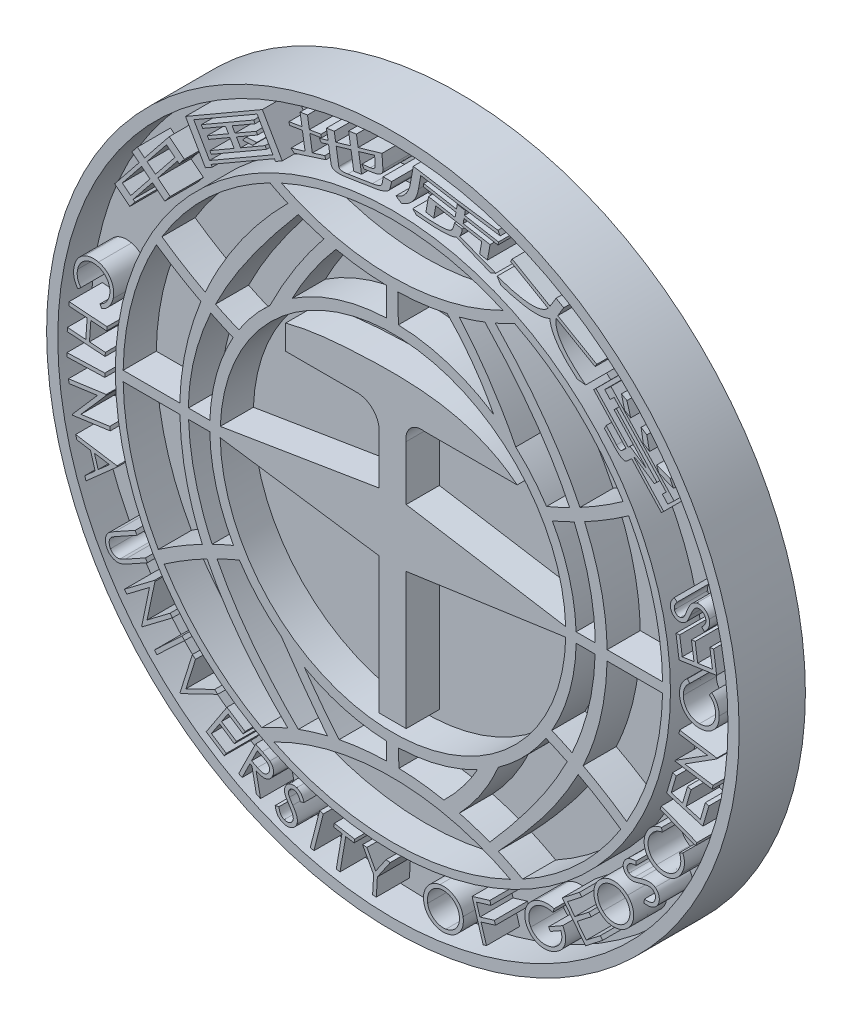
SolidWorks part; units mm, degrees
ref_plane "Front" through (0, 0, 0) normal (0, 0, 1) x (1, 0, 0)
ref_plane "Top" through (0, 0, 0) normal (0, 1, 0) x (1, 0, 0)
ref_plane "Right" through (0, 0, 0) normal (1, 0, 0) x (0, 0, -1)
sketch "草图1" plane through (0, 0, 0) normal (0, 0, 1) x (1, 0, 0)
  line L0 (72.5399, 200.1553) -> (359.2066, 200.1553) construction
  line L1 (52.1486, 218.5466) -> (86.4216, 218.5466)
  line L2 (52.16, 212.6026) -> (86.4145, 212.6026)
  line L3 (325.7074, 218.5466) -> (337.24, 218.5466)
  line L4 (325.7487, 212.6026) -> (337.2001, 212.6026)
  line L5 (110.8064, 218.5466) -> (206.5687, 234.2539)
  line L6 (206.5687, 234.2539) -> (206.5687, 266.7516)
  line L7 (194.0896, 277.5655) -> (150.2952, 277.5655)
  line L8 (223.0983, 266.7516) -> (223.0983, 233.7949)
  line L9 (223.0983, 233.7949) -> (319.4076, 218.0851)
  line L10 (110.7625, 212.6026) -> (206.5687, 198.8439)
  line L11 (206.5687, 198.8439) -> (206.5687, 116.6105)
  line L12 (206.5687, 116.6105) -> (223.0983, 116.6105)
  line L13 (223.0983, 116.6105) -> (223.0983, 198.8439)
  line L14 (223.0983, 198.8439) -> (319.4359, 212.6026)
  line L15 (206.5687, 229.1203) -> (206.5687, 204.7561)
  line L16 (223.0983, 229.1203) -> (223.0983, 204.7561)
  line L17 (118.5333, 216.4839) -> (302.6281, 214.9458)
  line L18 (206.5687, 204.7561) -> (118.5333, 216.4839)
  line L19 (223.0983, 229.1203) -> (302.6281, 214.9458)
  line L20 (206.5687, 229.1203) -> (118.5333, 216.4839)
  line L21 (302.6281, 214.9458) -> (223.0983, 204.7561)
  line L22 (150.2952, 277.5655) -> (150.2952, 292.3398)
  line L23 (233.9122, 277.5655) -> (290.0968, 277.5655)
  line L24 (211.1653, 342.4793) -> (211.1653, 325.4066)
  line L25 (217.9778, 342.492) -> (218.3833, 325.4278)
  line L26 (211.1653, 104.2036) -> (211.1653, 93.6862)
  line L27 (218.3833, 104.1824) -> (218.696, 93.6516)
  line L28 (91.5867, 218.5466) -> (104.4911, 218.5466)
  line L29 (91.6507, 212.6026) -> (104.4497, 212.6026)
  line L30 (344.4431, 218.5466) -> (377.9495, 218.5466)
  line L31 (344.4305, 212.6026) -> (377.9381, 212.6026)
  arc A0 (72.2414, 294.306) -> (52.1486, 218.5466) centre (215.049, 215.8866) ccw
  circle A1 centre (215.049, 215.8866) radius 167.6583
  circle A2 centre (215.049, 215.8866) radius 202.4027
  circle A3 centre (215.049, 215.8866) radius 209.1476
  arc A4 (110.7625, 212.6026) -> (319.4359, 212.6026) centre (215.0992, 214.8051) ccw
  arc A5 (118.5333, 268.8716) -> (104.4911, 218.5466) centre (215.0992, 214.8051) ccw
  arc A6 (147.7094, 364.2409) -> (281.5821, 364.6044) centre (214.2831, 497.9847) ccw
  arc A7 (140.7952, 360.9038) -> (151.6429, 355.6195) centre (214.2831, 497.9847) ccw
  arc A8 (143.2009, 69.6625) -> (286.0089, 69.2294) centre (214.1874, -68.2114) cw
  arc A9 (135.8554, 73.5068) -> (151.6429, 81.1477) centre (214.1874, -68.2114) cw
  arc A10 (75.5826, 300.1051) -> (101.7026, 284.1628) centre (214.2831, 497.9847) ccw
  arc A11 (72.2414, 294.306) -> (99.092, 278.0032) centre (214.2831, 497.9847) ccw
  arc A12 (76.8759, 129.5626) -> (102.8378, 145.2606) centre (214.1874, -68.2114) cw
  arc A13 (73.3718, 135.4427) -> (99.9338, 151.4478) centre (214.1874, -68.2114) cw
  arc A14 (307.8485, 275.185) -> (321.7916, 281.5682) centre (214.2831, 497.9847) ccw
  arc A15 (311.352, 269.4272) -> (324.5431, 275.4907) centre (214.2831, 497.9847) ccw
  arc A16 (311.0489, 159.6524) -> (323.2645, 154.0637) centre (214.1874, -68.2114) cw
  arc A17 (307.4201, 153.7722) -> (320.2998, 147.9117) centre (214.1874, -68.2114) cw
  arc A18 (140.7952, 360.9038) -> (75.5826, 300.1051) centre (215.049, 215.8866) ccw
  arc A19 (281.5821, 364.6044) -> (147.7094, 364.2409) centre (215.049, 215.8866) ccw
  arc A20 (307.8485, 275.185) -> (289.2417, 296.97) centre (215.0992, 214.8051) ccw
  arc A21 (354.0561, 300.8612) -> (288.5143, 361.3049) centre (215.049, 215.8866) ccw
  arc A22 (311.0489, 159.6524) -> (325.7487, 212.6026) centre (215.0992, 214.8051) ccw
  arc A23 (356.2357, 134.5849) -> (377.9381, 212.6026) centre (215.049, 215.8866) ccw
  arc A24 (293.3776, 73.0291) -> (352.6961, 128.7261) centre (215.049, 215.8866) ccw
  arc A25 (143.2009, 69.6625) -> (286.0089, 69.2294) centre (215.049, 215.8866) ccw
  arc A26 (76.8759, 129.5626) -> (135.8554, 73.5068) centre (215.049, 215.8866) ccw
  arc A27 (122.387, 154.3683) -> (147.7094, 127.0169) centre (215.0992, 214.8051) ccw
  arc A28 (194.0896, 277.5655) -> (206.5687, 266.7516) centre (193.3288, 264.0803) cw
  arc A29 (223.0983, 266.7516) -> (233.9122, 277.5655) centre (232.2503, 268.4135) cw
  arc A30 (107.9272, 280.9995) -> (122.0034, 274.6494) centre (214.2831, 497.9847) ccw
  arc A31 (105.075, 274.9725) -> (118.5333, 268.8716) centre (214.2831, 497.9847) ccw
  arc A32 (104.4497, 212.6026) -> (118.7962, 160.2717) centre (215.0992, 214.8051) ccw
  arc A33 (105.8575, 154.4288) -> (118.7962, 160.2717) centre (214.1874, -68.2114) cw
  arc A34 (108.8297, 148.2806) -> (122.387, 154.3683) centre (214.1874, -68.2114) cw
  arc A35 (157.9437, 83.6326) -> (175.4759, 89.0189) centre (214.1874, -68.2114) cw
  arc A36 (182.5568, 90.595) -> (211.1653, 93.6862) centre (214.1874, -68.2114) cw
  arc A37 (161.6302, 117.9071) -> (211.1653, 104.2036) centre (215.0992, 214.8051) ccw
  arc A38 (218.3833, 104.1824) -> (266.1481, 116.6105) centre (215.0992, 214.8051) ccw
  arc A39 (218.696, 93.6516) -> (245.818, 90.595) centre (214.1874, -68.2114) cw
  arc A40 (255.1803, 88.4396) -> (273.5693, 82.433) centre (214.1874, -68.2114) cw
  arc A41 (278.7221, 124.2497) -> (307.4201, 153.7722) centre (215.0992, 214.8051) ccw
  arc A42 (278.7221, 80.2986) -> (293.3776, 73.0291) centre (214.1874, -68.2114) cw
  arc A43 (326.9355, 144.5253) -> (352.6961, 128.7261) centre (214.1874, -68.2114) cw
  arc A44 (329.9546, 150.6539) -> (356.2357, 134.5849) centre (214.1874, -68.2114) cw
  arc A45 (325.7074, 218.5466) -> (311.352, 269.4272) centre (215.0992, 214.8051) ccw
  arc A46 (377.9495, 218.5466) -> (357.4288, 295.0803) centre (215.049, 215.8866) ccw
  arc A47 (328.0407, 284.7867) -> (354.0561, 300.8612) centre (214.2831, 497.9847) ccw
  arc A48 (330.8301, 278.7185) -> (357.4288, 295.0803) centre (214.2831, 497.9847) ccw
  arc A49 (275.8971, 307.281) -> (218.3833, 325.4278) centre (215.0992, 214.8051) ccw
  arc A50 (255.1803, 347.9212) -> (270.6225, 353.0105) centre (214.2831, 497.9847) ccw
  arc A51 (276.9233, 355.6195) -> (288.5143, 361.3049) centre (214.2831, 497.9847) ccw
  arc A52 (217.9778, 342.492) -> (247.9004, 346.1245) centre (214.2831, 497.9847) ccw
  arc A53 (211.1653, 325.4066) -> (154.3013, 307.281) centre (215.0992, 214.8051) ccw
  arc A54 (180.6658, 346.1245) -> (211.1653, 342.4793) centre (214.2831, 497.9847) ccw
  arc A55 (157.9437, 353.0105) -> (173.3859, 347.9212) centre (214.2831, 497.9847) ccw
  arc A56 (140.7952, 296.8239) -> (122.0034, 274.6494) centre (215.0992, 214.8051) ccw
  arc A57 (52.16, 212.6026) -> (73.3718, 135.4427) centre (215.049, 215.8866) ccw
  arc A58 (319.4076, 218.0851) -> (110.8064, 218.5466) centre (215.0992, 214.8051) ccw
  spline S0 degree 3 poles (151.6429, 355.6195) (131.4754, 335.4827) (113.6139, 311.0072) (101.7026, 284.1628) knots 0 0 0 0 0.28068 0.28068 0.28068 0.28068
  spline S1 degree 3 poles (157.9437, 353.0105) (140.1456, 331.9182) (121.0416, 307.5667) (107.9272, 280.9995) knots 0 0 0 0 0.285436 0.285436 0.285436 0.285436
  spline S2 degree 2 poles (173.3859, 347.9212) (154.2744, 324.1501) (140.7952, 296.8239) knots 0 0 0 1 1 1
  spline S3 degree 2 poles (180.6658, 346.1245) (165.244, 328.188) (154.3013, 307.281) knots 0 0 0 1 1 1
  spline S4 degree 2 poles (247.9004, 346.1245) (264.8675, 328.7744) (275.8971, 307.281) knots 0 0 0 1 1 1
  spline S5 degree 3 poles (255.1803, 347.9212) (268.2542, 332.7319) (279.6617, 315.7843) (289.0006, 297.447) (289.2417, 296.97) knots 0 0 0 0 1 1.026652 1.026652 1.026652 1.026652
  spline S6 degree 3 poles (270.6225, 353.0105) (290.1335, 332.4962) (309.1243, 308.2849) (321.7916, 281.5682) knots 0 0 0 0 0.286799 0.286799 0.286799 0.286799
  spline S7 degree 3 poles (276.9233, 355.6195) (296.5769, 335.1636) (315.3269, 311.2358) (328.0407, 284.7867) knots 0 0 0 0 0.27965 0.27965 0.27965 0.27965
  spline S8 degree 2 poles (147.7094, 127.0169) (160.9175, 107.521) (175.4759, 89.0189) knots 0 0 0 1 1 1
  spline S9 degree 2 poles (182.5568, 90.595) (171.495, 103.7926) (161.6302, 117.9071) knots 0 0 0 1 1 1
  spline S10 degree 2 poles (245.818, 90.595) (257.8098, 102.1756) (266.1481, 116.6105) knots 0 0 0 1 1 1
  spline S11 degree 2 poles (255.1803, 88.4396) (270.1846, 104.1922) (278.7221, 124.2497) knots 0 0 0 1 1 1
  spline S12 degree 3 poles (150.2952, 292.3398) (165.8888, 296.4461) (192.0674, 298.5248) (240.1904, 299.437) (272.5336, 291.8839) (290.0968, 277.5655) knots 0 0 0 0 0.33284 0.543658 1 1 1 1
  spline S13 degree 3 poles (99.092, 278.0032) (92.7565, 262.3211) (87.5994, 242.4643) (86.493, 222.0805) (86.4216, 218.5466) knots 0.302007 0.302007 0.302007 0.302007 0.463873 0.49775 0.49775 0.49775 0.49775
  spline S14 degree 3 poles (105.075, 274.9725) (98.4205, 260.2704) (92.6775, 241.5277) (91.6299, 222.0861) (91.5867, 218.5466) knots 0.306887 0.306887 0.306887 0.306887 0.462924 0.497524 0.497524 0.497524 0.497524
  spline S15 degree 3 poles (86.4145, 212.6026) (86.7161, 195.6195) (90.4987, 174.5636) (98.296, 155.1317) (99.9338, 151.4478) knots 0.516731 0.516731 0.516731 0.516731 0.679363 0.718188 0.718188 0.718188 0.718188
  spline S16 degree 3 poles (91.6507, 212.6026) (92.1947, 196.3415) (96.5469, 176.2512) (104.3036, 157.8109) (105.8575, 154.4288) knots 0.516867 0.516867 0.516867 0.516867 0.675459 0.711799 0.711799 0.711799 0.711799
  spline S17 degree 3 poles (108.8297, 148.2806) (121.1393, 124.0229) (138.8809, 102.6921) (157.9437, 83.6326) knots 0.734043 0.734043 0.734043 0.734043 1 1 1 1
  spline S18 degree 3 poles (102.8378, 145.2606) (114.7937, 121.0661) (132.4536, 99.6239) (151.6429, 81.1477) knots 0.74013 0.74013 0.74013 0.74013 1 1 1 1
  spline S19 degree 3 poles (320.2998, 147.9117) (308.1912, 123.9188) (290.9054, 102.2507) (273.5693, 82.433) knots 0.737687 0.737687 0.737687 0.737687 1 1 1 1
  spline S20 degree 3 poles (326.9355, 144.5253) (314.6021, 120.678) (296.8447, 99.5298) (278.7221, 80.2986) knots 0.742617 0.742617 0.742617 0.742617 1 1 1 1
  spline S21 degree 3 poles (337.2001, 212.6026) (336.8674, 200.436) (333.7541, 180.1993) (326.6191, 161.3731) (323.2645, 154.0637) knots 0.518698 0.518698 0.518698 0.518698 0.63684 0.715451 0.715451 0.715451 0.715451
  spline S22 degree 3 poles (344.4305, 212.6026) (344.0807, 196.2975) (340.2172, 174.865) (332.1053, 155.2499) (329.9546, 150.6539) knots 0.517484 0.517484 0.517484 0.517484 0.672121 0.72078 0.72078 0.72078 0.72078
  spline S23 degree 3 poles (324.5431, 275.4907) (329.8597, 263.1632) (335.5924, 244.3857) (337.1528, 224.7768) (337.24, 218.5466) knots 0.308395 0.308395 0.308395 0.308395 0.438918 0.499455 0.499455 0.499455 0.499455
  spline S24 degree 3 poles (330.8301, 278.7185) (336.0906, 266.726) (342.3821, 246.9766) (344.3106, 226.2145) (344.4431, 218.5466) knots 0.300884 0.300884 0.300884 0.300884 0.425898 0.498687 0.498687 0.498687 0.498687
sketch "草图2" plane through (0, 0, 0) normal (0, 0, 1) x (1, 0, 0)
  line L0 (188.3142, 411.8132) -> (193.0314, 412.5606)
  line L1 (193.0314, 412.5606) -> (194.0733, 405.9952)
  line L2 (194.0733, 405.9952) -> (208.4731, 410.1902)
  line L3 (203.9688, 406.922) -> (194.3746, 404.0863)
  line L4 (194.3746, 404.0863) -> (196.124, 393.0715)
  line L5 (196.124, 393.0715) -> (191.4068, 392.3241)
  line L6 (191.4068, 392.3241) -> (189.7545, 402.7291)
  line L7 (189.7545, 402.7291) -> (180.811, 400.0868)
  line L8 (180.811, 400.0868) -> (182.3719, 390.2384)
  line L9 (187.8285, 389.0737) -> (202.6423, 391.4224)
  line L10 (204.2168, 389.69) -> (186.9817, 386.9602)
  line L11 (177.7085, 389.1676) -> (176.1922, 398.722)
  line L12 (176.1922, 398.722) -> (171.7525, 397.4162)
  line L13 (171.7525, 397.4162) -> (170.669, 399.1742)
  line L14 (170.669, 399.1742) -> (175.8801, 400.6909)
  line L15 (175.8801, 400.6909) -> (174.9393, 406.624)
  line L16 (174.9393, 406.624) -> (179.6571, 407.3677)
  line L17 (179.6571, 407.3677) -> (180.5036, 402.0294)
  line L18 (180.5036, 402.0294) -> (189.4531, 404.638)
  line L19 (189.4531, 404.638) -> (188.3142, 411.8132)
  line L20 (162.0164, 388.0327) -> (160.4115, 398.1713)
  line L21 (160.4115, 398.1713) -> (152.6108, 396.9365)
  line L22 (152.6108, 396.9365) -> (152.3291, 398.7134)
  line L23 (152.3291, 398.7134) -> (160.1298, 399.9482)
  line L24 (160.1298, 399.9482) -> (159.0056, 407.0409)
  line L25 (159.0056, 407.0409) -> (163.4813, 407.7531)
  line L26 (163.4813, 407.7531) -> (164.6055, 400.6604)
  line L27 (164.6055, 400.6604) -> (171.6194, 401.7706)
  line L28 (171.6194, 401.7706) -> (171.9011, 399.9937)
  line L29 (171.9011, 399.9937) -> (164.8872, 398.8835)
  line L30 (164.8872, 398.8835) -> (166.3949, 389.3779)
  line L31 (155.502, 383.7715) -> (153.4982, 385.4584)
  line L32 (308.7779, 379.3725) -> (286.0675, 392.4842)
  line L33 (286.0675, 392.4842) -> (287.0738, 394.2276)
  line L34 (287.0738, 394.2276) -> (309.9727, 381.0065)
  line L35 (313.6015, 386.9864) -> (318.2295, 384.3133)
  line L36 (314.5992, 378.3368) -> (338.1861, 364.7158)
  line L37 (338.1861, 364.7158) -> (337.1798, 362.9724)
  line L38 (337.1798, 362.9724) -> (313.5117, 376.6372)
  line L39 (236.5785, 401.6343) -> (252.6436, 398.8009)
  line L40 (252.6436, 398.8009) -> (253.1624, 401.7382)
  line L41 (253.1624, 401.7382) -> (233.3542, 405.2319)
  line L42 (233.3542, 405.2319) -> (233.6671, 407.0043)
  line L43 (233.6671, 407.0043) -> (253.4753, 403.5107)
  line L44 (253.4753, 403.5107) -> (253.9614, 406.2703)
  line L45 (253.9614, 406.2703) -> (258.7925, 405.4202)
  line L46 (258.7925, 405.4202) -> (258.3064, 402.6607)
  line L47 (258.3064, 402.6607) -> (278.84, 399.0405)
  line L48 (278.84, 399.0405) -> (278.5271, 397.268)
  line L49 (278.5271, 397.268) -> (257.9935, 400.8882)
  line L50 (257.9935, 400.8882) -> (257.4747, 397.9509)
  line L51 (257.4747, 397.9509) -> (273.7212, 395.0859)
  line L52 (273.7212, 395.0859) -> (272.1518, 386.1743)
  line L53 (272.1518, 386.1743) -> (267.442, 387.006)
  line L54 (267.442, 387.006) -> (268.7021, 394.1463)
  line L55 (268.7021, 394.1463) -> (240.9778, 399.0349)
  line L56 (240.9778, 399.0349) -> (239.7177, 391.8945)
  line L57 (239.7177, 391.8945) -> (235.0091, 392.7226)
  line L58 (235.0091, 392.7226) -> (236.5785, 401.6343)
  line L59 (278.5118, 404.971) -> (279.8577, 402.6988)
  line L60 (231.8738, 410.271) -> (230.5061, 402.4989)
  line L61 (225.6422, 403.1713) -> (227.3556, 412.8935)
  line L62 (277.1751, 381.8172) -> (274.2504, 380.401)
  line L63 (252.2223, 395.6904) -> (256.9309, 394.8623)
  line L64 (337.6784, 351.7956) -> (357.232, 330.8254)
  line L65 (357.232, 330.8254) -> (358.2835, 331.8055)
  line L66 (358.2835, 331.8055) -> (368.2894, 325.1356)
  line L67 (368.2894, 325.1356) -> (348.6509, 346.1962)
  line L68 (348.6509, 346.1962) -> (350.0221, 347.4757)
  line L69 (350.0221, 347.4757) -> (374.5506, 321.1735)
  line L70 (374.5506, 321.1735) -> (372.975, 319.7045)
  line L71 (372.975, 319.7045) -> (361.032, 327.5784)
  line L72 (361.032, 327.5784) -> (360.6166, 327.1951)
  line L73 (360.6166, 327.1951) -> (378.5831, 307.9287)
  line L74 (378.5831, 307.9287) -> (377.2119, 306.6492)
  line L75 (377.2119, 306.6492) -> (359.2454, 325.9157)
  line L76 (359.2454, 325.9157) -> (356.4126, 323.2717)
  line L77 (353.3089, 327.1631) -> (355.8608, 329.5459)
  line L78 (355.8608, 329.5459) -> (336.3072, 350.5162)
  line L79 (336.3072, 350.5162) -> (337.6784, 351.7956)
  line L80 (346.7555, 357.415) -> (384.863, 316.5497)
  line L81 (384.863, 316.5497) -> (381.0723, 313.0127)
  line L82 (381.0723, 313.0127) -> (377.7726, 316.5526)
  line L83 (377.7726, 316.5526) -> (380.1921, 318.8101)
  line L84 (380.1921, 318.8101) -> (348.6892, 352.5945)
  line L85 (348.6892, 352.5945) -> (346.2697, 350.337)
  line L86 (346.2697, 350.337) -> (342.9648, 353.878)
  line L87 (342.9648, 353.878) -> (346.7555, 357.415)
  line L88 (382.4692, 327.1331) -> (384.4833, 322.9792)
  line L89 (375.7673, 326.4933) -> (374.2961, 330.067)
  line L90 (364.9632, 345.1561) -> (368.3921, 342.9067)
  line L91 (370.0533, 334.9896) -> (366.2763, 337.5004)
  line L92 (353.1213, 356.7271) -> (356.3901, 354.8412)
  line L93 (358.6824, 346.9206) -> (354.9408, 349.1284)
  line L94 (47.0129, 313.5334) -> (61.7843, 331.9671)
  line L95 (61.7843, 331.9671) -> (57.4207, 335.4618)
  line L96 (57.4207, 335.4618) -> (60.7172, 339.5776)
  line L97 (60.7172, 339.5776) -> (65.0808, 336.0829)
  line L98 (65.0808, 336.0829) -> (80.0046, 354.7072)
  line L99 (80.0046, 354.7072) -> (89.128, 347.3977)
  line L100 (89.128, 347.3977) -> (85.9802, 343.4724)
  line L101 (85.9802, 343.4724) -> (84.8979, 344.3413)
  line L102 (84.8979, 344.3413) -> (73.1219, 329.6424)
  line L103 (73.1219, 329.6424) -> (80.5648, 323.682)
  line L104 (80.5648, 323.682) -> (77.2683, 319.5662)
  line L105 (77.2683, 319.5662) -> (69.8254, 325.5265)
  line L106 (69.8254, 325.5265) -> (58.202, 311.0182)
  line L107 (58.202, 311.0182) -> (59.2843, 310.1493)
  line L108 (59.2843, 310.1493) -> (56.1364, 306.224)
  line L109 (56.1364, 306.224) -> (47.0129, 313.5334)
  line L110 (78.3354, 349.5967) -> (66.5594, 334.8977)
  line L111 (66.5594, 334.8977) -> (71.6433, 330.8276)
  line L112 (71.6433, 330.8276) -> (83.4192, 345.5265)
  line L113 (83.4192, 345.5265) -> (78.3354, 349.5967)
  line L114 (56.7233, 312.2034) -> (68.3468, 326.7118)
  line L115 (68.3468, 326.7118) -> (63.2629, 330.7819)
  line L116 (63.2629, 330.7819) -> (51.6395, 316.2735)
  line L117 (51.6395, 316.2735) -> (56.7233, 312.2034)
  line L118 (89.777, 370.1514) -> (136.2149, 396.9624)
  line L119 (136.2149, 396.9624) -> (148.241, 376.1343)
  line L120 (148.241, 376.1343) -> (144.1555, 373.7757)
  line L121 (144.1555, 373.7757) -> (143.5088, 374.8945)
  line L122 (143.5088, 374.8945) -> (105.2456, 352.801)
  line L123 (105.2456, 352.801) -> (105.9057, 351.6604)
  line L124 (105.9057, 351.6604) -> (101.8165, 349.3015)
  line L125 (101.8165, 349.3015) -> (89.777, 370.1514)
  line L126 (133.0419, 393.0182) -> (94.7788, 370.9247)
  line L127 (94.7788, 370.9247) -> (104.3335, 354.3828)
  line L128 (104.3335, 354.3828) -> (142.5966, 376.4763)
  line L129 (142.5966, 376.4763) -> (133.0419, 393.0182)
  line L130 (104.5298, 359.6743) -> (119.1805, 368.1335)
  line L131 (119.1805, 368.1335) -> (116.6249, 372.5539)
  line L132 (116.6249, 372.5539) -> (103.8328, 365.1684)
  line L133 (103.8328, 365.1684) -> (102.9569, 366.6844)
  line L134 (102.9569, 366.6844) -> (115.749, 374.07)
  line L135 (115.749, 374.07) -> (114.0235, 377.0623)
  line L136 (114.0235, 377.0623) -> (100.2217, 369.0967)
  line L137 (100.2217, 369.0967) -> (99.3416, 370.6162)
  line L138 (99.3416, 370.6162) -> (130.9758, 388.8783)
  line L139 (130.9758, 388.8783) -> (131.8559, 387.3588)
  line L140 (131.8559, 387.3588) -> (117.9485, 379.3306)
  line L141 (117.9485, 379.3306) -> (119.6739, 376.3383)
  line L142 (119.6739, 376.3383) -> (132.5169, 383.755)
  line L143 (132.5169, 383.755) -> (133.3928, 382.239)
  line L144 (133.3928, 382.239) -> (120.5498, 374.8222)
  line L145 (120.5498, 374.8222) -> (123.1055, 370.4018)
  line L146 (123.1055, 370.4018) -> (137.8617, 378.9236)
  line L147 (137.8617, 378.9236) -> (138.7377, 377.4075)
  line L148 (138.7377, 377.4075) -> (105.4057, 358.1582)
  line L149 (105.4057, 358.1582) -> (104.5298, 359.6743)
  line L150 (124.1387, 374.9886) -> (126.5695, 377.6412)
  line L151 (132.9341, 378.1337) -> (130.3869, 375.3218)
  spline S0 degree 3 poles (208.4731, 410.1902) (208.537, 409.3837) (208.6376, 408.2034) (208.7504, 406.6679) (208.8289, 405.603) (208.8963, 404.5943) (208.9716, 403.3633) (209.014, 402.4683) (209.0418, 401.8915) knots 0 0 0 0 0.291791 0.427178 0.555227 0.676899 0.791743 1 1 1 1
  spline S1 degree 3 poles (209.0418, 401.8915) (209.056, 401.6133) (209.0358, 401.1973) (208.8948, 400.6688) (208.7466, 400.2958) (208.5382, 399.9478) (208.2921, 399.6129) (207.9862, 399.3042) (207.6338, 399.014) (207.2343, 398.739) (206.7818, 398.4918) (206.2828, 398.2592) (205.7335, 398.0463) (205.1352, 397.8514) (204.2419, 397.6132) (203.5393, 397.4833) (203.0563, 397.3994) knots 0 0 0 0 0.101587 0.150006 0.198636 0.247194 0.297255 0.349619 0.404917 0.463286 0.525883 0.592406 0.663604 0.740193 0.821423 1 1 1 1
  spline S2 degree 2 poles (203.0563, 397.3994) (200.3399, 396.9452) (197.616, 396.5386) knots 0 0 0 1 1 1
  spline S3 degree 3 poles (197.616, 396.5386) (197.4314, 396.8517) (197.0351, 397.5168) (196.6029, 398.1591) (196.3761, 398.501) knots 0 0 0 0 0.46977 1 1 1 1
  spline S4 degree 3 poles (196.3761, 398.501) (197.285, 398.596) (198.9687, 398.7862) (200.6461, 399.0266) (201.4171, 399.1474) knots 0 0 0 0 0.539359 1 1 1 1
  spline S5 degree 3 poles (201.4171, 399.1474) (201.6644, 399.1799) (202.0192, 399.2552) (202.4741, 399.3699) (202.7777, 399.4689) (203.0526, 399.5871) (203.3068, 399.7051) (203.531, 399.8442) (203.7308, 399.9899) (203.9014, 400.1513) (204.0525, 400.319) (204.1689, 400.505) (204.2661, 400.6982) (204.3339, 400.9062) (204.3893, 401.2054) (204.3951, 401.4385) (204.376, 401.5945) knots 0 0 0 0 0.17408 0.253334 0.327784 0.396921 0.462405 0.523403 0.58097 0.634898 0.687305 0.738187 0.787727 0.838173 0.890438 1 1 1 1
  spline S6 degree 3 poles (204.376, 401.5945) (204.3768, 402.4347) (204.2983, 404.2166) (204.0984, 405.9887) (203.9688, 406.922) knots 0 0 0 0 0.471313 1 1 1 1
  spline S7 degree 3 poles (182.3719, 390.2384) (182.396, 390.0804) (182.4718, 389.8489) (182.6573, 389.5874) (182.83, 389.4132) (183.0421, 389.2639) (183.2931, 389.1388) (183.5787, 389.0307) (183.9036, 388.9513) (184.2633, 388.8858) (184.663, 388.8524) (185.0988, 388.8327) (185.5724, 388.8366) (186.0831, 388.8625) (186.8412, 388.929) (187.4266, 389.0096) (187.8285, 389.0737) knots 0 0 0 0 0.078918 0.117597 0.157218 0.199304 0.244912 0.295194 0.349582 0.409635 0.475295 0.547187 0.62474 0.708739 0.799318 1 1 1 1
  spline S8 degree 3 poles (202.6423, 391.4224) (203.0807, 391.489) (203.7164, 391.6035) (204.5311, 391.7877) (205.0847, 391.9217) (205.5963, 392.0719) (206.0672, 392.2279) (206.4965, 392.393) (206.8844, 392.5663) (207.234, 392.7463) (207.5385, 392.9407) (207.8069, 393.1377) (208.0281, 393.3489) (208.2159, 393.5639) (208.4023, 393.8632) (208.4907, 394.1083) (208.5133, 394.2761) knots 0 0 0 0 0.193901 0.282315 0.365275 0.442942 0.515378 0.582164 0.644008 0.701109 0.753928 0.801877 0.846407 0.887448 0.926387 1 1 1 1
  spline S9 degree 3 poles (208.5133, 394.2761) (208.681, 394.8905) (208.9422, 396.211) (209.0786, 397.5497) (209.1243, 398.2559) knots 0 0 0 0 0.473491 1 1 1 1
  spline S10 degree 2 poles (209.1243, 398.2559) (211.6921, 398.2378) (214.259, 398.3113) knots 0 0 0 1 1 1
  spline S11 degree 3 poles (214.259, 398.3113) (214.1207, 397.5274) (213.832, 396.1086) (213.4588, 394.7093) (213.2534, 394.0908) knots 0 0 0 0 0.549992 1 1 1 1
  spline S12 degree 3 poles (213.2534, 394.0908) (213.1677, 393.8257) (212.9818, 393.4387) (212.6365, 392.9696) (212.3136, 392.6304) (211.9396, 392.3046) (211.5131, 391.9913) (211.0281, 391.6979) (210.4885, 391.4164) (209.8933, 391.1497) (209.2453, 390.8944) (208.5416, 390.6588) (207.7834, 390.4351) (206.9699, 390.2257) (205.7795, 389.9543) (204.8525, 389.7928) (204.2168, 389.69) knots 0 0 0 0 0.079707 0.121905 0.166358 0.213522 0.263793 0.3177 0.375685 0.437973 0.504392 0.575029 0.650432 0.7307 0.815553 1 1 1 1
  spline S13 degree 3 poles (186.9817, 386.9602) (186.3008, 386.8551) (185.3102, 386.7139) (184.0246, 386.617) (183.1582, 386.5732) (182.3544, 386.5796) (181.614, 386.6138) (180.9374, 386.6938) (180.3241, 386.812) (179.7741, 386.9685) (179.286, 387.1637) (178.8602, 387.3985) (178.4961, 387.6716) (178.1993, 387.9885) (177.8849, 388.4679) (177.7543, 388.8832) (177.7085, 389.1676) knots 0 0 0 0 0.197962 0.287044 0.370216 0.446996 0.51779 0.582995 0.642478 0.696971 0.746973 0.793125 0.836243 0.877124 0.917171 1 1 1 1
  spline S14 degree 2 poles (153.4982, 385.4584) (157.7597, 386.7377) (162.0164, 388.0327) knots 0 0 0 1 1 1
  spline S15 degree 2 poles (166.3949, 389.3779) (170.1739, 390.5589) (173.9511, 391.7459) knots 0 0 0 1 1 1
  spline S16 degree 3 poles (173.9511, 391.7459) (174.0451, 391.4161) (174.2483, 390.7959) (174.5253, 390.2048) (174.6761, 389.9358) knots 0 0 0 0 0.526665 1 1 1 1
  spline S17 degree 2 poles (174.6761, 389.9358) (165.0759, 386.8946) (155.502, 383.7715) knots 0 0 0 1 1 1
  spline S18 degree 3 poles (277.9996, 380.7176) (278.9831, 380.3639) (280.4506, 379.8756) (282.3864, 379.2512) (283.7836, 378.8213) (285.1465, 378.4281) (286.4738, 378.061) (287.7662, 377.7252) (289.0245, 377.4208) (290.2481, 377.1492) (291.4362, 376.9016) (292.5906, 376.6925) (293.7082, 376.5098) (294.7919, 376.3581) (295.8419, 376.2413) (296.8573, 376.1509) (297.8366, 376.0943) (298.7812, 376.0624) (299.6906, 376.0731) (300.566, 376.1044) (301.4065, 376.1669) (302.2119, 376.2682) (302.9833, 376.3906) (303.7192, 376.5528) (304.4216, 376.7373) (305.0884, 376.9594) (305.7192, 377.2124) (306.3194, 377.4895) (306.8812, 377.8041) (307.4089, 378.1491) (308.0637, 378.6458) (308.5069, 379.0708) (308.7779, 379.3725) knots 0 0 0 0 0.097268 0.143936 0.189306 0.233312 0.275946 0.317476 0.357579 0.396434 0.434121 0.470519 0.505612 0.539514 0.572348 0.603929 0.634385 0.663633 0.691872 0.71901 0.745145 0.770285 0.794544 0.8178 0.84039 0.862108 0.883161 0.903623 0.923587 0.943024 0.962265 1 1 1 1
  spline S19 degree 2 poles (309.9727, 381.0065) (311.8534, 383.9562) (313.6015, 386.9864) knots 0 0 0 1 1 1
  spline S20 degree 2 poles (318.2295, 384.3133) (316.4809, 381.2846) (314.5992, 378.3368) knots 0 0 0 1 1 1
  spline S21 degree 3 poles (313.5117, 376.6372) (313.4478, 376.1715) (313.4129, 375.4642) (313.4286, 374.5163) (313.4831, 373.794) (313.5804, 373.0649) (313.7142, 372.3266) (313.8983, 371.5846) (314.1137, 370.8317) (314.3731, 370.0723) (314.672, 369.3053) (315.0117, 368.5311) (315.3919, 367.7495) (315.8131, 366.9595) (316.275, 366.1623) (316.7761, 365.3584) (317.3205, 364.5493) (317.8974, 363.7273) (318.5238, 362.9014) (319.1873, 362.0652) (319.8932, 361.2231) (320.6395, 360.3758) (321.4208, 359.5161) (322.2479, 358.6538) (323.1168, 357.784) (324.0188, 356.8992) (324.9696, 356.0164) (325.9549, 355.119) (326.9836, 354.2173) (328.0564, 353.3107) (329.5485, 352.0656) (330.7126, 351.1579) (331.4957, 350.5431) knots 0 0 0 0 0.042736 0.064358 0.086261 0.108623 0.131285 0.154514 0.178177 0.202538 0.227529 0.253082 0.27947 0.306615 0.334553 0.363316 0.392821 0.423299 0.454707 0.487158 0.520449 0.554711 0.589923 0.626177 0.663451 0.701821 0.741174 0.781536 0.823119 0.865676 0.90937 1 1 1 1
  spline S22 degree 3 poles (331.4957, 350.5431) (330.9719, 350.6159) (330.2111, 350.7155) (329.2296, 350.8388) (328.5681, 350.9082) (327.9569, 350.9678) (327.2425, 351.0318) (326.7304, 351.0564) (326.4057, 351.0689) knots 0 0 0 0 0.309862 0.44967 0.579682 0.699641 0.809557 1 1 1 1
  spline S23 degree 3 poles (326.4057, 351.0689) (325.7663, 351.5947) (324.8295, 352.3912) (323.6104, 353.4633) (322.7322, 354.2534) (321.8842, 355.0408) (321.068, 355.8274) (320.2748, 356.6025) (319.511, 357.3746) (318.7813, 358.1457) (318.075, 358.9094) (317.3982, 359.6684) (316.7513, 360.4244) (316.132, 361.1739) (315.5392, 361.9177) (314.9769, 362.6587) (314.4475, 363.3985) (313.9379, 364.128) (313.4608, 364.8563) (313.0155, 365.5805) (312.596, 366.2988) (312.2037, 367.011) (311.8428, 367.7218) (311.5089, 368.4261) (311.201, 369.1252) (310.9245, 369.82) (310.6817, 370.5123) (310.4572, 371.1968) (310.2662, 371.8788) (310.1063, 372.5573) (309.9289, 373.4483) (309.836, 374.1186) (309.7953, 374.5641) knots 0 0 0 0 0.0843 0.125216 0.165334 0.204611 0.243054 0.280772 0.317555 0.353654 0.388882 0.423493 0.457212 0.490212 0.522505 0.554071 0.584928 0.615146 0.644689 0.673578 0.701724 0.729402 0.756364 0.7829 0.808775 0.834144 0.85904 0.883473 0.907497 0.931149 0.954443 1 1 1 1
  spline S24 degree 3 poles (309.7953, 374.5641) (309.4533, 374.3722) (308.9114, 374.1251) (308.1627, 373.8305) (307.5651, 373.6364) (306.942, 373.464) (306.2945, 373.3063) (305.6204, 373.1784) (304.9203, 373.0716) (304.1945, 372.9874) (303.4422, 372.9175) (302.6631, 372.8773) (301.8577, 372.857) (301.0273, 372.8584) (300.171, 372.885) (299.2886, 372.9302) (298.3799, 372.9972) (297.4456, 373.0897) (296.4849, 373.2009) (295.497, 373.3323) (294.4848, 373.4965) (293.4448, 373.6714) (292.3797, 373.8705) (291.2882, 374.0936) (290.1712, 374.3415) (289.0255, 374.6029) (287.8577, 374.8997) (286.6602, 375.2034) (285.4405, 375.5443) (284.1907, 375.8918) (282.475, 376.4102) (281.1734, 376.8037) (280.303, 377.0927) knots 0 0 0 0 0.038844 0.059015 0.079762 0.101124 0.12312 0.145831 0.169146 0.19334 0.218279 0.244068 0.27069 0.298167 0.326403 0.355644 0.385791 0.416749 0.448752 0.4817 0.515567 0.55044 0.586289 0.623021 0.660923 0.699751 0.739563 0.780412 0.822261 0.865154 0.90906 1 1 1 1
  spline S25 degree 3 poles (280.303, 377.0927) (280.1668, 377.3204) (279.9497, 377.6823) (279.6375, 378.1865) (279.3609, 378.62) (279.062, 379.0932) (278.6072, 379.7979) (278.2479, 380.3423) (277.9996, 380.7176) knots 0 0 0 0 0.185331 0.294745 0.414209 0.544467 0.68566 1 1 1 1
  spline S26 degree 3 poles (227.3556, 412.8935) (229.7574, 412.4758) (233.3315, 411.8562) (238.06, 411.0576) (241.5194, 410.4855) (244.9191, 409.9252) (248.2623, 409.3852) (251.547, 408.8606) (254.7745, 408.3628) (257.9417, 407.8728) (261.0514, 407.4042) (264.1026, 406.9512) (267.0975, 406.5235) (270.0328, 406.1082) (273.8297, 405.5794) (276.6511, 405.2161) (278.5118, 404.971) knots 0 0 0 0 0.141267 0.210204 0.277889 0.344455 0.409869 0.474132 0.537211 0.599105 0.65985 0.719445 0.777859 0.835156 0.891239 1 1 1 1
  spline S27 degree 3 poles (279.8577, 402.6988) (276.0022, 403.2552) (270.1861, 404.1273) (262.3845, 405.3202) (256.4233, 406.252) (250.3883, 407.2109) (242.1958, 408.5464) (236.016, 409.5694) (231.8738, 410.271) knots 0 0 0 0 0.240564 0.363189 0.48739 0.613167 0.740556 1 1 1 1
  spline S28 degree 3 poles (230.5061, 402.4989) (230.361, 401.718) (230.1147, 400.5672) (229.6343, 399.1007) (229.2372, 398.0687) (228.7847, 397.0911) (228.2736, 396.1696) (227.7116, 395.2995) (227.0983, 394.4796) (226.4272, 393.7179) (225.7043, 393.0085) (224.9289, 392.3527) (224.0968, 391.7519) (223.2138, 391.203) (221.9478, 390.5374) (220.943, 390.1279) (220.2495, 389.8962) knots 0 0 0 0 0.139032 0.205365 0.269736 0.332348 0.393637 0.453893 0.513406 0.57255 0.631282 0.690422 0.750008 0.810638 0.872129 1 1 1 1
  spline S29 degree 2 poles (220.2495, 389.8962) (218.617, 391.087) (216.9174, 392.1798) knots 0 0 0 1 1 1
  spline S30 degree 3 poles (216.9174, 392.1798) (217.5013, 392.358) (218.3484, 392.686) (219.413, 393.2355) (220.1592, 393.6943) (220.8611, 394.2027) (221.5187, 394.7636) (222.1312, 395.3771) (222.6994, 396.0411) (223.2277, 396.7528) (223.7003, 397.5224) (224.143, 398.3362) (224.5291, 399.2058) (224.8792, 400.1222) (225.2891, 401.4389) (225.5157, 402.4682) (225.6422, 403.1713) knots 0 0 0 0 0.123329 0.183047 0.241881 0.300165 0.358004 0.416334 0.475162 0.53446 0.595241 0.657501 0.721517 0.787347 0.855631 1 1 1 1
  spline S31 degree 3 poles (256.9309, 394.8623) (256.8591, 394.3487) (256.7367, 393.6077) (256.4981, 392.6747) (256.311, 392.0633) (256.0968, 391.5152) (255.7939, 390.8933) (255.5228, 390.475) (255.3103, 390.2394) knots 0 0 0 0 0.313732 0.453378 0.582071 0.700116 0.808797 1 1 1 1
  spline S32 degree 3 poles (255.3103, 390.2394) (258.9218, 388.8936) (266.2287, 386.1342) (273.4989, 383.2795) (277.1751, 381.8172) knots 0 0 0 0 0.493454 1 1 1 1
  spline S33 degree 3 poles (274.2504, 380.401) (272.4306, 381.1722) (269.7228, 382.3132) (266.1356, 383.7929) (263.5193, 384.8639) (260.9477, 385.8946) (257.6169, 387.2154) (255.1408, 388.1883) (253.4992, 388.8089) knots 0 0 0 0 0.264817 0.393673 0.519917 0.643574 0.764863 1 1 1 1
  spline S34 degree 3 poles (253.4992, 388.8089) (253.2668, 388.6934) (252.8943, 388.5499) (252.3798, 388.3661) (251.954, 388.2412) (251.5031, 388.1198) (251.024, 388.0135) (250.5203, 387.9133) (249.9902, 387.8213) (249.4337, 387.7374) (248.8508, 387.6595) (248.2405, 387.5964) (247.6038, 387.537) (246.9401, 387.4944) (246.2505, 387.4494) (245.5339, 387.4216) (244.7905, 387.3969) (244.0206, 387.389) (243.2242, 387.3794) (242.4009, 387.3843) (241.5522, 387.4021) (240.6766, 387.4215) (239.7749, 387.4541) (238.8451, 387.4938) (237.8896, 387.5386) (236.9085, 387.6029) (235.9003, 387.6597) (234.866, 387.7447) (233.8032, 387.8222) (232.7155, 387.9188) (231.2107, 388.0479) (230.0715, 388.171) (229.3016, 388.2467) knots 0 0 0 0 0.031858 0.04905 0.06717 0.086397 0.106451 0.127495 0.149542 0.172603 0.196689 0.221838 0.248031 0.275309 0.303607 0.333007 0.363473 0.395056 0.42767 0.461409 0.49628 0.532041 0.569089 0.607228 0.646461 0.686697 0.728122 0.770614 0.814295 0.859136 0.904877 1 1 1 1
  spline S35 degree 3 poles (229.3016, 388.2467) (228.9732, 388.6115) (228.2306, 389.3958) (227.4573, 390.1497) (227.0309, 390.5557) knots 0 0 0 0 0.454632 1 1 1 1
  spline S36 degree 3 poles (227.0309, 390.5557) (227.8016, 390.4683) (228.9435, 390.3505) (230.4472, 390.1999) (231.5294, 390.0972) (232.5826, 390.0031) (233.6054, 389.9179) (234.5989, 389.8377) (235.5617, 389.7681) (236.4945, 389.7121) (237.3975, 389.6533) (238.2706, 389.6106) (239.1141, 389.5751) (239.9272, 389.5486) (240.7111, 389.5266) (241.4647, 389.5175) (242.1879, 389.5139) (242.8808, 389.5157) (243.5445, 389.5298) (244.1778, 389.5516) (244.7821, 389.5767) (245.3557, 389.6144) (245.8996, 389.6654) (246.4141, 389.7143) (246.8991, 389.776) (247.3529, 389.8499) (247.778, 389.9287) (248.1733, 390.0136) (248.5373, 390.1109) (248.8726, 390.2144) (249.2654, 390.3534) (249.5371, 390.4843) (249.704, 390.5781) knots 0 0 0 0 0.101816 0.150688 0.198379 0.244519 0.289481 0.333111 0.375349 0.416198 0.455779 0.494131 0.530945 0.566594 0.600923 0.633882 0.665525 0.695856 0.724832 0.752663 0.779034 0.804232 0.828107 0.850738 0.872067 0.892277 0.911079 0.928818 0.94534 0.960514 0.974871 1 1 1 1
  spline S37 degree 3 poles (249.704, 390.5781) (250.035, 390.7281) (250.4889, 391.0819) (250.9672, 391.7149) (251.304, 392.306) (251.5944, 393.0039) (251.9522, 394.1297) (252.1219, 395.0476) (252.2223, 395.6904) knots 0 0 0 0 0.183422 0.286624 0.401121 0.527831 0.669483 1 1 1 1
  spline S38 degree 3 poles (356.4126, 323.2717) (356.2375, 323.1053) (355.9361, 322.9047) (355.4848, 322.7433) (355.127, 322.6915) (354.749, 322.6939) (354.3505, 322.7564) (353.9303, 322.875) (353.4914, 323.0542) (353.033, 323.2917) (352.5484, 323.5797) (352.046, 323.9327) (351.5233, 324.3421) (350.9772, 324.8063) (350.1923, 325.5273) (349.6167, 326.123) (349.2258, 326.5378) knots 0 0 0 0 0.083502 0.12375 0.165133 0.208108 0.254275 0.304462 0.359056 0.418239 0.483196 0.554229 0.630794 0.713216 0.802469 1 1 1 1
  spline S39 degree 3 poles (349.2258, 326.5378) (348.7442, 327.0508) (348.0141, 327.8421) (347.0169, 328.9173) (346.2269, 329.7741) (345.4035, 330.6611) (344.2553, 331.9148) (343.3751, 332.8679) (342.7843, 333.5194) knots 0 0 0 0 0.222224 0.340028 0.463108 0.590278 0.722258 1 1 1 1
  spline S40 degree 3 poles (342.7843, 333.5194) (342.98, 333.7982) (343.3777, 334.4581) (343.703, 335.1564) (343.8811, 335.5462) knots 0 0 0 0 0.442572 1 1 1 1
  spline S41 degree 3 poles (343.8811, 335.5462) (344.9187, 334.3293) (346.9805, 331.9788) (349.068, 329.6511) (350.1053, 328.5297) knots 0 0 0 0 0.511458 1 1 1 1
  spline S42 degree 3 poles (350.1053, 328.5297) (350.4243, 328.1919) (350.8804, 327.722) (351.5348, 327.2429) (351.9558, 327.0139) (352.3453, 326.8818) (352.8244, 326.8578) (353.1497, 327.0053) (353.3089, 327.1631) knots 0 0 0 0 0.363321 0.5084 0.631377 0.736232 0.826716 1 1 1 1
  spline S43 degree 3 poles (374.2961, 330.067) (375.6559, 329.4987) (378.3535, 328.4422) (381.1063, 327.5392) (382.4692, 327.1331) knots 0 0 0 0 0.508934 1 1 1 1
  spline S44 degree 3 poles (384.4833, 322.9792) (383.0696, 323.5313) (380.165, 324.7046) (377.2597, 325.876) (375.7673, 326.4933) knots 0 0 0 0 0.484465 1 1 1 1
  spline S45 degree 3 poles (368.3921, 342.9067) (368.7321, 341.5649) (369.348, 338.9381) (369.8418, 336.2856) (370.0533, 334.9896) knots 0 0 0 0 0.513188 1 1 1 1
  spline S46 degree 3 poles (366.2763, 337.5004) (366.2111, 338.0782) (366.094, 338.9594) (365.9174, 340.1536) (365.7623, 341.0952) (365.5898, 342.0672) (365.3255, 343.4249) (365.1134, 344.4579) (364.9632, 345.1561) knots 0 0 0 0 0.22444 0.343204 0.466009 0.59288 0.724296 1 1 1 1
  spline S47 degree 3 poles (356.3901, 354.8412) (356.8253, 353.5389) (357.6294, 350.9095) (358.3516, 348.2565) (358.6824, 346.9206) knots 0 0 0 0 0.499443 1 1 1 1
  spline S48 degree 3 poles (354.9408, 349.1284) (354.6974, 350.4347) (354.1563, 352.9844) (353.4874, 355.5037) (353.1213, 356.7271) knots 0 0 0 0 0.509943 1 1 1 1
  spline S49 degree 3 poles (126.5695, 377.6412) (127.1584, 377.7021) (128.0256, 377.803) (129.166, 377.9018) (129.9758, 377.9745) (130.7579, 378.0285) (131.7398, 378.0887) (132.4626, 378.1195) (132.9341, 378.1337) knots 0 0 0 0 0.278174 0.410074 0.537795 0.660158 0.778367 1 1 1 1
  spline S50 degree 3 poles (130.3869, 375.3218) (129.3014, 375.3193) (127.2154, 375.253) (125.134, 375.0977) (124.1387, 374.9886) knots 0 0 0 0 0.520191 1 1 1 1
sketch "草图4" plane through (0, 0, 0) normal (0, 0, 1) x (1, 0, 0)
  line L0 (403.1707, 257.3856) -> (401.5489, 258.9711)
  line L1 (384.9206, 266.0525) -> (386.7645, 264.6072)
  line L2 (387.8985, 234.9285) -> (386.0265, 247.9378)
  line L3 (386.0265, 247.9378) -> (388.2645, 248.2607)
  line L4 (388.2645, 248.2607) -> (389.8099, 237.5171)
  line L5 (389.8099, 237.5171) -> (396.907, 238.5403)
  line L6 (396.907, 238.5403) -> (395.3753, 249.1917)
  line L7 (395.3753, 249.1917) -> (397.6001, 249.5105)
  line L8 (397.6001, 249.5105) -> (399.1317, 238.8591)
  line L9 (399.1317, 238.8591) -> (408.0338, 240.1402)
  line L10 (408.0338, 240.1402) -> (406.5021, 250.7916)
  line L11 (406.5021, 250.7916) -> (408.7401, 251.1145)
  line L12 (408.7401, 251.1145) -> (410.5983, 238.1973)
  line L13 (410.5983, 238.1973) -> (387.8985, 234.9285)
  line L14 (392.9515, 227.6091) -> (394.3347, 225.8109)
  line L15 (406.189, 225.8506) -> (407.5445, 227.6574)
  line L16 (408.0059, 177.3075) -> (385.4685, 180.7563)
  line L17 (385.4685, 180.7563) -> (385.545, 181.247)
  line L18 (385.545, 181.247) -> (405.085, 193.5902)
  line L19 (405.085, 193.5902) -> (387.8353, 196.2274)
  line L20 (387.8353, 196.2274) -> (388.1767, 198.4517)
  line L21 (388.1767, 198.4517) -> (410.714, 195.0029)
  line L22 (410.714, 195.0029) -> (410.6373, 194.4976)
  line L23 (410.6373, 194.4976) -> (391.3209, 182.242)
  line L24 (391.3209, 182.242) -> (408.36, 179.632)
  line L25 (408.36, 179.632) -> (408.0059, 177.3075)
  line L26 (380.3658, 161.5234) -> (384.0366, 174.0689)
  line L27 (384.0366, 174.0689) -> (386.1953, 173.4377)
  line L28 (386.1953, 173.4377) -> (383.1653, 163.0827)
  line L29 (383.1653, 163.0827) -> (390.006, 161.0837)
  line L30 (390.006, 161.0837) -> (393.0104, 171.349)
  line L31 (393.0104, 171.349) -> (395.1531, 170.7225)
  line L32 (395.1531, 170.7225) -> (392.1487, 160.4573)
  line L33 (392.1487, 160.4573) -> (400.7357, 157.9467)
  line L34 (400.7357, 157.9467) -> (403.7401, 168.212)
  line L35 (403.7401, 168.212) -> (405.8988, 167.5807)
  line L36 (405.8988, 167.5807) -> (402.2536, 155.125)
  line L37 (402.2536, 155.125) -> (380.3658, 161.5234)
  line L38 (376.4188, 151.0984) -> (377.2593, 153.2343)
  line L39 (377.2593, 153.2343) -> (398.6604, 144.8033)
  line L40 (398.6604, 144.8033) -> (397.8199, 142.6673)
  line L41 (397.8199, 142.6673) -> (376.4188, 151.0984)
  line L42 (377.2988, 141.988) -> (377.6684, 139.7547)
  line L43 (388.1218, 134.1965) -> (390.1685, 135.1451)
  line L44 (366.7406, 97.1253) -> (366.9313, 99.3853)
  line L45 (361.8179, 116.6937) -> (361.876, 114.3603)
  line L46 (317.3461, 75.2193) -> (327.702, 83.2804)
  line L47 (327.702, 83.2804) -> (329.09, 81.4982)
  line L48 (329.09, 81.4982) -> (320.5401, 74.842)
  line L49 (320.5401, 74.842) -> (324.9414, 69.192)
  line L50 (324.9414, 69.192) -> (333.417, 75.7918)
  line L51 (333.417, 75.7918) -> (334.7908, 74.0245)
  line L52 (334.7908, 74.0245) -> (326.3152, 67.4247)
  line L53 (326.3152, 67.4247) -> (331.8348, 60.3389)
  line L54 (331.8348, 60.3389) -> (340.3105, 66.9386)
  line L55 (340.3105, 66.9386) -> (341.6985, 65.1564)
  line L56 (341.6985, 65.1564) -> (331.4169, 57.1517)
  line L57 (331.4169, 57.1517) -> (317.3461, 75.2193)
  line L58 (312.4491, 67.14) -> (311.7437, 64.8142)
  line L59 (316.4786, 57.6474) -> (310.1652, 54.0453)
  line L60 (310.1652, 54.0453) -> (309.0748, 55.9571)
  line L61 (309.0748, 55.9571) -> (317.6076, 60.8255)
  line L62 (262.8862, 48.7414) -> (273.6017, 52.0175)
  line L63 (273.6017, 52.0175) -> (274.2914, 49.7616)
  line L64 (274.2914, 49.7616) -> (265.5498, 47.089)
  line L65 (265.5498, 47.089) -> (267.6189, 40.3213)
  line L66 (267.6189, 40.3213) -> (276.3605, 42.9939)
  line L67 (276.3605, 42.9939) -> (277.0502, 40.738)
  line L68 (277.0502, 40.738) -> (268.3086, 38.0654)
  line L69 (268.3086, 38.0654) -> (271.5847, 27.3499)
  line L70 (271.5847, 27.3499) -> (269.6108, 26.7464)
  line L71 (269.6108, 26.7464) -> (262.8862, 48.7414)
  line L72 (196.7357, 42.7457) -> (199.3627, 42.5998)
  line L73 (199.3627, 42.5998) -> (204.6564, 32.8962)
  line L74 (204.6564, 32.8962) -> (210.9069, 41.9521)
  line L75 (210.9069, 41.9521) -> (213.5383, 41.8074)
  line L76 (213.5383, 41.8074) -> (205.6633, 30.3277)
  line L77 (205.6633, 30.3277) -> (205.0571, 19.4515)
  line L78 (205.0571, 19.4515) -> (202.8128, 19.5748)
  line L79 (202.8128, 19.5748) -> (203.419, 30.451)
  line L80 (203.419, 30.451) -> (196.7357, 42.7457)
  line L81 (179.2861, 43.1785) -> (179.6599, 45.3596)
  line L82 (179.6599, 45.3596) -> (191.9663, 43.2587)
  line L83 (191.9663, 43.2587) -> (191.5925, 41.0775)
  line L84 (191.5925, 41.0775) -> (186.5902, 41.933)
  line L85 (186.5902, 41.933) -> (183.1316, 21.6811)
  line L86 (183.1316, 21.6811) -> (180.8444, 22.0707)
  line L87 (180.8444, 22.0707) -> (184.303, 42.3226)
  line L88 (184.303, 42.3226) -> (179.2861, 43.1785)
  line L89 (170.8172, 47.5329) -> (173.0285, 46.9659)
  line L90 (173.0285, 46.9659) -> (167.3532, 24.8559)
  line L91 (167.3532, 24.8559) -> (165.1419, 25.4229)
  line L92 (165.1419, 25.4229) -> (170.8172, 47.5329)
  line L93 (143.959, 36.8381) -> (146.1844, 37.2968)
  line L94 (161.367, 47.0938) -> (159.1338, 46.3773)
  line L95 (132.1283, 63.1204) -> (136.2312, 61.0938)
  line L96 (132.4452, 49.2406) -> (135.1185, 35.9896)
  line L97 (135.1185, 35.9896) -> (132.5646, 37.2516)
  line L98 (132.5646, 37.2516) -> (129.9085, 50.4934)
  line L99 (129.9085, 50.4934) -> (128.7338, 51.0737)
  line L100 (128.7338, 51.0737) -> (123.9946, 41.4874)
  line L101 (123.9946, 41.4874) -> (121.9345, 42.5052)
  line L102 (121.9345, 42.5052) -> (132.1283, 63.1204)
  line L103 (133.1875, 60.0813) -> (129.7255, 53.0776)
  line L104 (129.7255, 53.0776) -> (133.2517, 51.2987)
  line L105 (136.8139, 58.2896) -> (133.1875, 60.0813)
  line L106 (114.8403, 73.6563) -> (125.7775, 66.4682)
  line L107 (125.7775, 66.4682) -> (124.5425, 64.5826)
  line L108 (124.5425, 64.5826) -> (115.5108, 70.5177)
  line L109 (115.5108, 70.5177) -> (111.5879, 64.5486)
  line L110 (111.5879, 64.5486) -> (120.5466, 58.6635)
  line L111 (120.5466, 58.6635) -> (119.3194, 56.7996)
  line L112 (119.3194, 56.7996) -> (110.3607, 62.6847)
  line L113 (110.3607, 62.6847) -> (105.4393, 55.1914)
  line L114 (105.4393, 55.1914) -> (114.3979, 49.3063)
  line L115 (114.3979, 49.3063) -> (113.1615, 47.4251)
  line L116 (113.1615, 47.4251) -> (102.2973, 54.5633)
  line L117 (102.2973, 54.5633) -> (114.8403, 73.6563)
  line L118 (93.9571, 90.7984) -> (95.8345, 89.1802)
  line L119 (95.8345, 89.1802) -> (90.0614, 70.9043)
  line L120 (90.0614, 70.9043) -> (107.3851, 79.2456)
  line L121 (107.3851, 79.2456) -> (109.2669, 77.6288)
  line L122 (109.2669, 77.6288) -> (86.875, 66.813)
  line L123 (86.875, 66.813) -> (86.5013, 67.1371)
  line L124 (86.5013, 67.1371) -> (93.9571, 90.7984)
  line L125 (87.6721, 97.3864) -> (89.2422, 95.7176)
  line L126 (89.2422, 95.7176) -> (72.5646, 80.0001)
  line L127 (72.5646, 80.0001) -> (70.9944, 81.6689)
  line L128 (70.9944, 81.6689) -> (87.6721, 97.3864)
  line L129 (52.8949, 104.4123) -> (71.0622, 118.157)
  line L130 (71.0622, 118.157) -> (71.3613, 117.7618)
  line L131 (71.3613, 117.7618) -> (66.592, 95.1628)
  line L132 (66.592, 95.1628) -> (80.4985, 105.6825)
  line L133 (80.4985, 105.6825) -> (81.8557, 103.8909)
  line L134 (81.8557, 103.8909) -> (63.6884, 90.1462)
  line L135 (63.6884, 90.1462) -> (63.3751, 90.5563)
  line L136 (63.3751, 90.5563) -> (68.0513, 112.9245)
  line L137 (68.0513, 112.9245) -> (54.317, 102.5345)
  line L138 (54.317, 102.5345) -> (52.8949, 104.4123)
  line L139 (59.3882, 138.4612) -> (60.4967, 136.4587)
  line L140 (60.4967, 136.4587) -> (48.376, 129.7418)
  line L141 (53.517, 120.4589) -> (65.6377, 127.1757)
  line L142 (65.6377, 127.1757) -> (66.752, 125.1701)
  line L143 (66.752, 125.1701) -> (54.6313, 118.4532)
  line L144 (47.2675, 131.7444) -> (59.3882, 138.4612)
  line L145 (48.6103, 166.2125) -> (29.7067, 149.4868)
  line L146 (29.7067, 149.4868) -> (29.0107, 151.842)
  line L147 (29.0107, 151.842) -> (35.2048, 157.4262)
  line L148 (35.2048, 157.4262) -> (32.4058, 166.8807)
  line L149 (32.4058, 166.8807) -> (24.1729, 168.1698)
  line L150 (24.1729, 168.1698) -> (23.4487, 170.6175)
  line L151 (23.4487, 170.6175) -> (48.4504, 166.7514)
  line L152 (48.4504, 166.7514) -> (48.6103, 166.2125)
  line L153 (43.8808, 165.1038) -> (34.8132, 166.5231)
  line L154 (34.8132, 166.5231) -> (37.0345, 159.0214)
  line L155 (37.0345, 159.0214) -> (43.8808, 165.1038)
  line L156 (19.1253, 197.6189) -> (41.8588, 200.7775)
  line L157 (41.8588, 200.7775) -> (41.928, 200.2832)
  line L158 (41.928, 200.2832) -> (26.6244, 182.7502)
  line L159 (26.6244, 182.7502) -> (44.0242, 185.1695)
  line L160 (44.0242, 185.1695) -> (44.3382, 182.9288)
  line L161 (44.3382, 182.9288) -> (21.6047, 179.7702)
  line L162 (21.6047, 179.7702) -> (21.5314, 180.2778)
  line L163 (21.5314, 180.2778) -> (36.6315, 197.6569)
  line L164 (36.6315, 197.6569) -> (19.4483, 195.2701)
  line L165 (19.4483, 195.2701) -> (19.1253, 197.6189)
  line L166 (41.0352, 211.5636) -> (41.1094, 209.2881)
  line L167 (41.1094, 209.2881) -> (18.2942, 208.5713)
  line L168 (18.2942, 208.5713) -> (18.22, 210.8467)
  line L169 (18.22, 210.8467) -> (41.0352, 211.5636)
  line L170 (42.3939, 236.4952) -> (42.2299, 234.1951)
  line L171 (42.2299, 234.1951) -> (32.6339, 234.8844)
  line L172 (32.6339, 234.8844) -> (31.8004, 223.2545)
  line L173 (31.8004, 223.2545) -> (41.3964, 222.5653)
  line L174 (41.3964, 222.5653) -> (41.228, 220.2638)
  line L175 (41.228, 220.2638) -> (18.3567, 221.905)
  line L176 (18.3567, 221.905) -> (18.5251, 224.2065)
  line L177 (18.5251, 224.2065) -> (29.5643, 223.414)
  line L178 (29.5643, 223.414) -> (30.3978, 235.0439)
  line L179 (30.3978, 235.0439) -> (19.3586, 235.8363)
  line L180 (19.3586, 235.8363) -> (19.5227, 238.1364)
  line L181 (19.5227, 238.1364) -> (42.3939, 236.4952)
  line L182 (39.1453, 244.2621) -> (38.1944, 246.3321)
  line L183 (26.5603, 248.9759) -> (24.82, 247.5139)
  spline S0 degree 3 poles (401.5489, 258.9711) (402.026, 259.4214) (402.6788, 260.1099) (403.365, 261.1056) (403.7359, 261.8097) (403.9892, 262.5032) (404.1701, 263.4066) (404.1171, 264.0904) (404.0009, 264.5194) knots 0 0 0 0 0.309214 0.444518 0.568272 0.682969 0.791021 1 1 1 1
  spline S1 degree 3 poles (404.0009, 264.5194) (403.9061, 264.8837) (403.7027, 265.4126) (403.2977, 266.0473) (402.9403, 266.4806) (402.5422, 266.8672) (402.1077, 267.1888) (401.6449, 267.4412) (401.1547, 267.6131) (400.6553, 267.7211) (399.9853, 267.7755) (399.4842, 267.7154) (399.1628, 267.6269) knots 0 0 0 0 0.176611 0.263282 0.352096 0.439473 0.52288 0.604879 0.685693 0.765655 0.843898 1 1 1 1
  spline S2 degree 3 poles (399.1628, 267.6269) (398.7862, 267.5352) (398.0501, 267.1801) (397.4462, 266.6314) (397.1767, 266.3066) knots 0 0 0 0 0.477634 1 1 1 1
  spline S3 degree 3 poles (397.1767, 266.3066) (396.9551, 266.0435) (396.6443, 265.6007) (396.2392, 264.9623) (395.9305, 264.395) (395.6008, 263.7791) (395.1592, 262.8357) (394.8297, 262.0983) (394.623, 261.58) knots 0 0 0 0 0.191188 0.300856 0.420541 0.550476 0.689606 1 1 1 1
  spline S4 degree 3 poles (394.623, 261.58) (394.4166, 261.0733) (394.1052, 260.3547) (393.696, 259.4499) (393.4171, 258.8833) (393.1713, 258.3852) (392.8715, 257.874) (392.6567, 257.5281) (392.4996, 257.3367) knots 0 0 0 0 0.345089 0.494003 0.626297 0.743452 0.844207 1 1 1 1
  spline S5 degree 3 poles (392.4996, 257.3367) (392.2998, 257.0766) (391.9625, 256.7266) (391.4831, 256.302) (391.1049, 256.028) (390.7113, 255.7843) (390.1546, 255.5162) (389.7206, 255.3512) (389.4194, 255.2772) knots 0 0 0 0 0.260297 0.386097 0.508979 0.631374 0.753909 1 1 1 1
  spline S6 degree 3 poles (389.4194, 255.2772) (388.9551, 255.1568) (388.2402, 255.0507) (387.2914, 255.124) (386.6002, 255.2633) (385.9366, 255.4987) (385.3115, 255.8227) (384.7341, 256.2368) (384.2044, 256.7286) (383.7357, 257.2893) (383.2072, 258.1192) (382.9419, 258.8131) (382.8158, 259.2903) knots 0 0 0 0 0.167227 0.248628 0.330198 0.411986 0.492878 0.574456 0.65853 0.743813 0.828109 1 1 1 1
  spline S7 degree 3 poles (382.8158, 259.2903) (382.6846, 259.8008) (382.5738, 260.5903) (382.6504, 261.6449) (382.781, 262.3) (382.9439, 262.8303) (383.1121, 263.2445) (383.3162, 263.6767) (383.5584, 264.1244) (383.8418, 264.5871) (384.2898, 265.239) (384.6534, 265.7294) (384.9206, 266.0525) knots 0 0 0 0 0.214228 0.320451 0.428175 0.484747 0.545531 0.609558 0.678804 0.752151 0.829788 1 1 1 1
  spline S8 degree 3 poles (386.7645, 264.6072) (386.5549, 264.3483) (386.2684, 263.9596) (385.9181, 263.4493) (385.6994, 263.1003) (385.5099, 262.774) (385.3511, 262.4675) (385.2332, 262.1783) (385.107, 261.8284) (385.0145, 261.3964) (384.9595, 260.702) (385.0226, 260.1803) (385.1134, 259.8434) knots 0 0 0 0 0.190102 0.275535 0.353222 0.425172 0.490893 0.550046 0.60335 0.703062 0.801064 1 1 1 1
  spline S9 degree 3 poles (385.1134, 259.8434) (385.221, 259.43) (385.474, 258.844) (386.0115, 258.2079) (386.4918, 257.8515) (387.0161, 257.5885) (387.7708, 257.4043) (388.3572, 257.4379) (388.7314, 257.5433) knots 0 0 0 0 0.26766 0.392563 0.517227 0.63971 0.75748 1 1 1 1
  spline S10 degree 3 poles (388.7314, 257.5433) (388.9692, 257.6074) (389.3205, 257.7349) (389.7501, 257.9841) (390.0641, 258.2063) (390.365, 258.4865) (390.7786, 258.9735) (391.064, 259.3898) (391.2383, 259.6973) knots 0 0 0 0 0.217405 0.327146 0.43722 0.555953 0.688608 1 1 1 1
  spline S11 degree 3 poles (391.2383, 259.6973) (391.3161, 259.8332) (391.4309, 260.081) (391.6025, 260.4596) (391.7703, 260.8537) (391.9631, 261.3217) (392.2754, 262.0904) (392.531, 262.6995) (392.6973, 263.1352) knots 0 0 0 0 0.125651 0.219154 0.333788 0.46958 0.625587 1 1 1 1
  spline S12 degree 3 poles (392.6973, 263.1352) (392.9179, 263.6701) (393.2369, 264.4486) (393.7114, 265.4258) (394.0536, 266.0735) (394.3995, 266.6602) (394.7403, 267.1886) (395.0833, 267.6575) (395.5381, 268.1898) (396.1218, 268.7613) (397.1046, 269.4921) (397.9229, 269.8709) (398.4909, 270.0135) knots 0 0 0 0 0.185936 0.270077 0.348927 0.421216 0.488813 0.550884 0.607686 0.713608 0.812548 1 1 1 1
  spline S13 degree 3 poles (398.4909, 270.0135) (398.8816, 270.1141) (399.4776, 270.2145) (400.2769, 270.2186) (400.8655, 270.1567) (401.4487, 270.0324) (402.0275, 269.847) (402.6004, 269.595) (403.163, 269.2897) (403.6969, 268.9312) (404.1939, 268.5351) (404.6319, 268.0885) (405.033, 267.6147) (405.3741, 267.0903) (405.7752, 266.336) (405.99, 265.7221) (406.0987, 265.3005) knots 0 0 0 0 0.121811 0.181349 0.240754 0.300093 0.361042 0.423838 0.488739 0.553968 0.617735 0.680149 0.742476 0.804812 0.868539 1 1 1 1
  spline S14 degree 3 poles (406.0987, 265.3005) (406.1884, 264.9706) (406.2813, 264.4712) (406.3375, 263.801) (406.3386, 263.3059) (406.3059, 262.813) (406.239, 262.3228) (406.1313, 261.8358) (405.9844, 261.3514) (405.7963, 260.8656) (405.566, 260.3765) (405.286, 259.8837) (404.9497, 259.3946) (404.5782, 258.8916) (403.9977, 258.2042) (403.5143, 257.7088) (403.1707, 257.3856) knots 0 0 0 0 0.114979 0.170537 0.226134 0.281426 0.336695 0.392471 0.449096 0.506896 0.567636 0.630891 0.697406 0.767291 0.841266 1 1 1 1
  spline S15 degree 3 poles (394.3347, 225.8109) (394.0222, 225.5623) (393.5657, 225.1799) (393.0171, 224.6134) (392.6369, 224.1749) (392.2823, 223.7196) (391.9596, 223.2441) (391.6665, 222.7492) (391.3189, 222.0642) (390.9508, 221.1716) (390.5455, 219.6463) (390.4205, 218.4557) (390.4313, 217.6509) knots 0 0 0 0 0.127711 0.189876 0.251838 0.313116 0.374208 0.435352 0.496789 0.619589 0.743099 1 1 1 1
  spline S16 degree 3 poles (390.4313, 217.6509) (390.4343, 217.2043) (390.4714, 216.538) (390.6184, 215.6656) (390.758, 215.0266) (390.9442, 214.4006) (391.1781, 213.7904) (391.4398, 213.1871) (391.7522, 212.605) (392.0874, 212.0407) (392.4659, 211.5136) (392.8624, 211.0121) (393.2892, 210.5446) (393.7473, 210.1131) (394.2293, 209.7126) (394.7408, 209.344) (395.2781, 209.0096) (395.8429, 208.7157) (396.4222, 208.453) (397.0203, 208.2347) (397.6361, 208.0626) (398.2658, 207.9201) (399.1391, 207.7929) (399.8056, 207.7554) (400.2544, 207.7566) knots 0 0 0 0 0.086184 0.128326 0.170513 0.212279 0.254128 0.29649 0.339013 0.381471 0.422966 0.464054 0.504729 0.544922 0.585341 0.625507 0.66644 0.707283 0.748216 0.789033 0.829949 0.871465 0.913464 1 1 1 1
  spline S17 degree 3 poles (400.2544, 207.7566) (400.9237, 207.754) (401.9124, 207.8492) (403.1839, 208.1475) (404.0794, 208.4639) (404.9272, 208.8768) (405.7373, 209.3688) (406.4992, 209.9571) (407.2097, 210.6266) (407.8599, 211.3597) (408.4232, 212.1524) (408.9074, 212.9875) (409.2989, 213.8715) (409.599, 214.8028) (409.89, 216.1266) (409.9625, 217.1581) (409.9632, 217.8553) knots 0 0 0 0 0.128068 0.189355 0.249699 0.309508 0.369636 0.430868 0.493471 0.556315 0.618193 0.679364 0.740863 0.802947 0.866417 1 1 1 1
  spline S18 degree 3 poles (409.9632, 217.8553) (409.9632, 218.6259) (409.8532, 219.7706) (409.4435, 221.2264) (409.0364, 222.2606) (408.494, 223.2371) (407.6163, 224.5021) (406.7931, 225.3406) (406.189, 225.8506) knots 0 0 0 0 0.253063 0.374588 0.495489 0.616994 0.740384 1 1 1 1
  spline S19 degree 3 poles (407.5445, 227.6574) (407.9039, 227.3779) (408.4193, 226.9287) (409.0421, 226.2698) (409.4847, 225.7565) (409.8831, 225.2073) (410.2645, 224.6394) (410.6025, 224.0378) (410.921, 223.4175) (411.1993, 222.7718) (411.4397, 222.1054) (411.6518, 221.4237) (411.8145, 220.7179) (411.9513, 219.997) (412.0784, 218.998) (412.1168, 218.2372) (412.1184, 217.7241) knots 0 0 0 0 0.120565 0.180573 0.239944 0.299872 0.360084 0.420947 0.482447 0.544638 0.606934 0.669959 0.733521 0.798585 0.864162 1 1 1 1
  spline S20 degree 3 poles (412.1184, 217.7241) (412.1152, 217.2394) (412.0926, 216.5189) (411.9952, 215.5738) (411.8814, 214.8942) (411.7487, 214.2329) (411.5761, 213.5933) (411.3777, 212.9727) (411.1421, 212.3743) (410.8837, 211.7914) (410.5863, 211.2313) (410.2656, 210.6859) (409.9104, 210.1636) (409.5195, 209.6624) (408.9596, 209.0136) (408.4928, 208.565) (408.1696, 208.2783) knots 0 0 0 0 0.137493 0.204234 0.269292 0.332834 0.395438 0.45706 0.517532 0.577721 0.637777 0.697281 0.757072 0.816767 0.877432 1 1 1 1
  spline S21 degree 3 poles (408.1696, 208.2783) (407.6222, 207.8013) (406.7388, 207.1643) (405.4621, 206.4896) (404.4672, 206.0729) (403.4268, 205.7508) (401.9613, 205.4433) (400.8264, 205.35) (400.06, 205.3508) knots 0 0 0 0 0.247102 0.369017 0.490904 0.613766 0.7392 1 1 1 1
  spline S22 degree 3 poles (400.06, 205.3508) (399.256, 205.3472) (398.0618, 205.4437) (396.5308, 205.8132) (395.4447, 206.1902) (394.4112, 206.6873) (393.4251, 207.2883) (392.49, 208.003) (391.6164, 208.8183) (390.8123, 209.7119) (390.1121, 210.6769) (389.5174, 211.6974) (389.0352, 212.7742) (388.6567, 213.9056) (388.2812, 215.512) (388.1905, 216.7676) (388.183, 217.6139) knots 0 0 0 0 0.126556 0.187439 0.247422 0.307113 0.36754 0.428837 0.491964 0.555324 0.617685 0.679234 0.74086 0.80299 0.866694 1 1 1 1
  spline S23 degree 3 poles (388.183, 217.6139) (388.1869, 218.1339) (388.2104, 218.9074) (388.3491, 219.9177) (388.4789, 220.6507) (388.6582, 221.3625) (388.8679, 222.0579) (389.1289, 222.7286) (389.4192, 223.382) (389.7462, 224.013) (390.1107, 224.6125) (390.5037, 225.1861) (390.9294, 225.7284) (391.3852, 226.2472) (392.0413, 226.8961) (392.5785, 227.3359) (392.9515, 227.6091) knots 0 0 0 0 0.135621 0.201173 0.265616 0.32952 0.39235 0.454799 0.516923 0.578622 0.639846 0.699665 0.759734 0.819385 0.879539 1 1 1 1
  spline S24 degree 3 poles (377.6684, 139.7547) (377.2738, 139.693) (376.694, 139.559) (375.9408, 139.3252) (375.3989, 139.1146) (374.8729, 138.8773) (374.3657, 138.6108) (373.8742, 138.3166) (373.4028, 137.9879) (372.948, 137.6347) (372.5197, 137.2492) (372.1069, 136.844) (371.7143, 136.4127) (371.3482, 135.9499) (370.8804, 135.297) (370.5722, 134.7725) (370.3786, 134.4136) knots 0 0 0 0 0.127673 0.190064 0.252119 0.31354 0.374529 0.435293 0.496661 0.558242 0.619349 0.680874 0.743219 0.805762 0.869531 1 1 1 1
  spline S25 degree 3 poles (370.3786, 134.4136) (370.173, 134.0165) (369.8908, 133.4118) (369.5988, 132.5771) (369.4326, 131.9449) (369.2986, 131.3069) (369.2047, 130.66) (369.1616, 130.0045) (369.1553, 129.3451) (369.1941, 128.6902) (369.2671, 128.0469) (369.3894, 127.4206) (369.5399, 126.8072) (369.7367, 126.2101) (369.9799, 125.6318) (370.2512, 125.0634) (370.5701, 124.516) (370.9222, 123.9888) (371.3128, 123.4887) (371.7368, 123.017) (372.1927, 122.57) (372.6837, 122.1508) (373.3893, 121.6208) (373.9631, 121.2774) (374.3583, 121.0658) knots 0 0 0 0 0.086353 0.128574 0.170529 0.212456 0.254368 0.296598 0.339169 0.381594 0.423174 0.464034 0.504704 0.545034 0.585244 0.625749 0.666526 0.707418 0.748053 0.788907 0.82977 0.871223 0.913444 1 1 1 1
  spline S26 degree 3 poles (374.3583, 121.0658) (374.9465, 120.7458) (375.8626, 120.3623) (377.125, 120.029) (378.0619, 119.8854) (379.0037, 119.8427) (379.9472, 119.9005) (380.8957, 120.0553) (381.8374, 120.3053) (382.7561, 120.6478) (383.6283, 121.0785) (384.4463, 121.5908) (385.2103, 122.1807) (385.9144, 122.8599) (386.7962, 123.889) (387.3506, 124.7626) (387.6765, 125.3785) knots 0 0 0 0 0.128213 0.189381 0.24979 0.309449 0.369686 0.430569 0.49329 0.556084 0.618102 0.679345 0.740718 0.802701 0.866457 1 1 1 1
  spline S27 degree 3 poles (387.6765, 125.3785) (388.0372, 126.0578) (388.4795, 127.1166) (388.8075, 128.5903) (388.9356, 129.6928) (388.9173, 130.8093) (388.7427, 132.3372) (388.4101, 133.4627) (388.1218, 134.1965) knots 0 0 0 0 0.25298 0.374398 0.495377 0.616946 0.740625 1 1 1 1
  spline S28 degree 3 poles (390.1685, 135.1451) (390.3486, 134.7284) (390.5913, 134.0918) (390.832, 133.2188) (390.9723, 132.5568) (391.069, 131.8856) (391.1341, 131.2066) (391.1549, 130.5168) (391.1384, 129.8194) (391.0776, 129.1178) (390.9781, 128.4169) (390.8404, 127.7172) (390.6562, 127.0187) (390.4329, 126.3209) (390.0724, 125.3828) (389.7472, 124.6953) (389.5077, 124.2425) knots 0 0 0 0 0.120374 0.180247 0.239925 0.299637 0.359923 0.420664 0.482465 0.544763 0.607238 0.670083 0.733698 0.79864 0.864201 1 1 1 1
  spline S29 degree 3 poles (389.5077, 124.2425) (389.2838, 123.8109) (388.9157, 123.1914) (388.3811, 122.4087) (387.9673, 121.8603) (387.5364, 121.3435) (387.0817, 120.8623) (386.6143, 120.4085) (386.1237, 119.9915) (385.623, 119.5974) (385.0958, 119.2466) (384.5549, 118.9199) (383.9937, 118.6288) (383.4151, 118.3694) (382.6138, 118.0662) (381.9907, 117.8927) (381.5693, 117.7925) knots 0 0 0 0 0.137929 0.204296 0.268897 0.332848 0.395125 0.45672 0.517615 0.577758 0.637457 0.697183 0.757022 0.816759 0.877034 1 1 1 1
  spline S30 degree 3 poles (381.5693, 117.7925) (380.8626, 117.6293) (379.7856, 117.4892) (378.3451, 117.492) (377.2746, 117.6048) (376.207, 117.8068) (374.7719, 118.2298) (373.7294, 118.6822) (373.0542, 119.0435) knots 0 0 0 0 0.247135 0.368898 0.490494 0.613735 0.738959 1 1 1 1
  spline S31 degree 3 poles (373.0542, 119.0435) (372.3424, 119.4182) (371.3363, 120.0678) (370.1649, 121.1196) (369.3861, 121.9636) (368.7073, 122.8855) (368.1275, 123.8827) (367.6425, 124.9531) (367.2541, 126.0845) (366.9718, 127.2507) (366.8122, 128.4292) (366.7628, 129.6061) (366.8475, 130.7823) (367.0442, 131.957) (367.4795, 133.5446) (367.9804, 134.6945) (368.3785, 135.4402) knots 0 0 0 0 0.12678 0.187579 0.247651 0.307424 0.367587 0.429088 0.492285 0.555803 0.617825 0.679397 0.741056 0.803283 0.866794 1 1 1 1
  spline S32 degree 3 poles (368.3785, 135.4402) (368.6224, 135.8994) (369.018, 136.5634) (369.6088, 137.3962) (370.075, 137.9765) (370.5694, 138.518) (371.0812, 139.0311) (371.6296, 139.4974) (372.1918, 139.9385) (372.7806, 140.333) (373.3835, 140.6915) (374.0004, 141.01) (374.63, 141.2916) (375.2764, 141.5259) (376.1596, 141.7897) (376.8391, 141.9285) (377.2988, 141.988) knots 0 0 0 0 0.135597 0.20129 0.266169 0.329572 0.392459 0.455048 0.517164 0.578741 0.639749 0.700008 0.759724 0.819491 0.879173 1 1 1 1
  spline S33 degree 3 poles (366.9313, 99.3853) (367.5814, 99.3076) (368.5257, 99.2345) (369.7283, 99.3426) (370.5077, 99.4959) (371.2036, 99.7448) (372.0091, 100.1898) (372.5125, 100.653) (372.767, 101.0201) knots 0 0 0 0 0.309144 0.443725 0.568043 0.682556 0.790593 1 1 1 1
  spline S34 degree 3 poles (372.767, 101.0201) (372.994, 101.3211) (373.2561, 101.8207) (373.4988, 102.5309) (373.6057, 103.0816) (373.6498, 103.6326) (373.6178, 104.171) (373.5142, 104.6859) (373.3395, 105.1757) (373.1043, 105.6297) (372.7237, 106.1837) (372.3529, 106.5248) (372.0879, 106.7241) knots 0 0 0 0 0.176437 0.263338 0.351795 0.439297 0.522428 0.604352 0.685249 0.765923 0.843967 1 1 1 1
  spline S35 degree 3 poles (372.0879, 106.7241) (371.7781, 106.9589) (371.0344, 107.2966) (370.2275, 107.4104) (369.8067, 107.4094) knots 0 0 0 0 0.478923 1 1 1 1
  spline S36 degree 3 poles (369.8067, 107.4094) (369.463, 107.4125) (368.9218, 107.3802) (368.1722, 107.2779) (367.5365, 107.1645) (366.8534, 107.0178) (365.8447, 106.7659) (365.0668, 106.5512) (364.5371, 106.3813) knots 0 0 0 0 0.191309 0.301387 0.421139 0.550744 0.690346 1 1 1 1
  spline S37 degree 3 poles (364.5371, 106.3813) (364.0143, 106.2212) (363.2642, 106) (362.3081, 105.739) (361.6967, 105.5887) (361.1527, 105.478) (360.571, 105.3656) (360.1651, 105.3206) (359.9182, 105.3208) knots 0 0 0 0 0.345291 0.493755 0.625881 0.74275 0.844282 1 1 1 1
  spline S38 degree 3 poles (359.9182, 105.3208) (359.5921, 105.3117) (359.1084, 105.3428) (358.4767, 105.4445) (358.0264, 105.5667) (357.5866, 105.7087) (357.0261, 105.9685) (356.6267, 106.2055) (356.3741, 106.3861) knots 0 0 0 0 0.259489 0.385312 0.508885 0.630751 0.75296 1 1 1 1
  spline S39 degree 3 poles (356.3741, 106.3861) (355.9832, 106.6651) (355.4565, 107.1559) (354.8988, 107.9262) (354.5689, 108.5485) (354.3281, 109.2094) (354.1808, 109.8973) (354.1301, 110.6063) (354.1766, 111.327) (354.3103, 112.0447) (354.6183, 112.9769) (354.9788, 113.6236) (355.2683, 114.0216) knots 0 0 0 0 0.167258 0.248673 0.330447 0.411916 0.493037 0.574839 0.658847 0.744079 0.828576 1 1 1 1
  spline S40 degree 3 poles (355.2683, 114.0216) (355.5748, 114.4512) (356.1178, 115.0333) (356.9785, 115.6471) (357.5677, 115.9613) (358.0815, 116.1687) (358.5056, 116.3085) (358.9691, 116.4229) (359.4677, 116.5236) (360.004, 116.5992) (360.7904, 116.6733) (361.4001, 116.688) (361.8179, 116.6937) knots 0 0 0 0 0.214448 0.320476 0.428601 0.485016 0.545593 0.60998 0.679003 0.752298 0.830054 1 1 1 1
  spline S41 degree 3 poles (361.876, 114.3603) (361.5435, 114.3482) (361.0609, 114.339) (360.4469, 114.2732) (360.0383, 114.2257) (359.668, 114.1571) (359.3308, 114.0886) (359.0339, 113.9955) (358.6855, 113.8659) (358.2939, 113.6624) (357.7214, 113.2682) (357.3657, 112.8826) (357.1623, 112.6012) knots 0 0 0 0 0.190493 0.275602 0.353157 0.425726 0.490947 0.549805 0.603507 0.703453 0.801244 1 1 1 1
  spline S42 degree 3 poles (357.1623, 112.6012) (356.9103, 112.2577) (356.6178, 111.6921) (356.473, 110.874) (356.5011, 110.2772) (356.6342, 109.706) (356.9598, 109.0034) (357.3643, 108.5775) (357.6798, 108.3559) knots 0 0 0 0 0.26778 0.39197 0.51756 0.640259 0.758075 1 1 1 1
  spline S43 degree 3 poles (357.6798, 108.3559) (357.8821, 108.2151) (358.2031, 108.0239) (358.6706, 107.8527) (359.0437, 107.7534) (359.4524, 107.7008) (360.0892, 107.6766) (360.5895, 107.7368) (360.9361, 107.7904) knots 0 0 0 0 0.217884 0.327117 0.438449 0.557897 0.6899 1 1 1 1
  spline S44 degree 3 poles (360.9361, 107.7904) (361.0899, 107.815) (361.3518, 107.8904) (361.7519, 108.0004) (362.165, 108.1149) (362.6485, 108.267) (363.4441, 108.5067) (364.0741, 108.7101) (364.5188, 108.8521) knots 0 0 0 0 0.124769 0.21848 0.333139 0.468726 0.625267 1 1 1 1
  spline S45 degree 3 poles (364.5188, 108.8521) (365.069, 109.0276) (365.8741, 109.2655) (366.9279, 109.5222) (367.6445, 109.6705) (368.3154, 109.7814) (368.9398, 109.8454) (369.5188, 109.8811) (370.0564, 109.8757) (370.5598, 109.8333) (371.0395, 109.7693) (371.499, 109.6734) (371.9375, 109.5463) (372.3576, 109.3956) (372.887, 109.1515) (373.2616, 108.9296) (373.4943, 108.7584) knots 0 0 0 0 0.185885 0.270059 0.348999 0.421349 0.488819 0.550918 0.607975 0.661671 0.71342 0.763638 0.812582 0.860231 0.907149 1 1 1 1
  spline S46 degree 3 poles (373.4943, 108.7584) (373.8152, 108.5165) (374.2834, 108.1312) (374.7839, 107.5095) (375.1189, 107.0204) (375.3868, 106.4884) (375.6167, 105.9251) (375.7816, 105.322) (375.9021, 104.6935) (375.9723, 104.0551) (375.9691, 103.4204) (375.9158, 102.7987) (375.7949, 102.1896) (375.6154, 101.5932) (375.2862, 100.8059) (374.9484, 100.2528) (374.6948, 99.8992) knots 0 0 0 0 0.121812 0.18153 0.240687 0.300578 0.361117 0.42424 0.489114 0.554364 0.617923 0.680568 0.742639 0.805186 0.868461 1 1 1 1
  spline S47 degree 3 poles (374.6948, 99.8992) (374.4966, 99.6228) (374.1687, 99.2368) (373.6943, 98.7616) (373.3082, 98.4512) (372.9139, 98.1564) (372.4899, 97.904) (372.0476, 97.6771) (371.5832, 97.4749) (371.0902, 97.3114) (370.5665, 97.1795) (370.0088, 97.0902) (369.4185, 97.0234) (368.796, 96.9994) (367.898, 97.0115) (367.2094, 97.0667) (366.7406, 97.1253) knots 0 0 0 0 0.114534 0.170583 0.226069 0.281421 0.336429 0.392193 0.448976 0.506993 0.567141 0.630856 0.697274 0.767356 0.840723 1 1 1 1
  spline S48 degree 3 poles (339.7079, 95.8039) (340.2881, 96.3968) (341.2057, 97.2239) (342.5687, 98.1016) (343.6109, 98.6476) (344.6996, 99.0711) (345.8282, 99.3802) (346.9979, 99.5848) (348.1964, 99.6645) (349.395, 99.6417) (350.5689, 99.5031) (351.7016, 99.2427) (352.7978, 98.8783) (353.8511, 98.3935) (355.2222, 97.59) (356.1576, 96.8236) (356.7437, 96.2618) knots 0 0 0 0 0.130995 0.193717 0.255294 0.31627 0.37758 0.439595 0.503234 0.566739 0.62845 0.689323 0.749754 0.810326 0.871873 1 1 1 1
  spline S49 degree 3 poles (356.7437, 96.2618) (357.3234, 95.7022) (358.1181, 94.8015) (358.9704, 93.4697) (359.4889, 92.4365) (359.9018, 91.3602) (360.2007, 90.2373) (360.3854, 89.0682) (360.4648, 87.8701) (360.4365, 86.6685) (360.2938, 85.4937) (360.0406, 84.3603) (359.6768, 83.2668) (359.1941, 82.2173) (358.3939, 80.8547) (357.6371, 79.9236) (357.0792, 79.3428) knots 0 0 0 0 0.128296 0.190222 0.251234 0.312007 0.37341 0.435852 0.500135 0.564303 0.626906 0.688221 0.748869 0.810001 0.871771 1 1 1 1
  spline S50 degree 3 poles (357.0792, 79.3428) (356.5193, 78.7502) (355.5996, 77.9609) (354.2644, 77.0886) (353.2238, 76.5651) (352.1453, 76.1437) (351.017, 75.8494) (349.8497, 75.6475) (348.6496, 75.572) (347.4511, 75.6019) (346.2798, 75.7337) (345.1529, 75.9856) (344.0684, 76.3456) (343.0283, 76.8195) (341.6773, 77.5987) (340.7648, 78.3553) (340.1881, 78.9002) knots 0 0 0 0 0.129825 0.19245 0.253838 0.315209 0.376707 0.439422 0.503803 0.568069 0.630346 0.691421 0.751821 0.812193 0.873351 1 1 1 1
  spline S51 degree 3 poles (340.1881, 78.9002) (339.7997, 79.273) (339.2577, 79.8679) (338.6081, 80.7139) (338.1759, 81.3747) (337.7865, 82.0585) (337.4466, 82.7694) (337.1417, 83.5028) (336.8928, 84.2607) (336.6922, 85.0309) (336.534, 85.8042) (336.44, 86.5792) (336.3898, 87.3518) (336.3964, 88.1231) (336.4572, 88.8934) (336.5604, 89.6655) (336.7291, 90.4312) (336.9378, 91.1869) (337.1943, 91.9219) (337.5025, 92.6299) (337.8507, 93.3161) (338.248, 93.9762) (338.8345, 94.8327) (339.3469, 95.4248) (339.7079, 95.8039) knots 0 0 0 0 0.085793 0.128093 0.169933 0.211575 0.253442 0.295495 0.33811 0.380504 0.422336 0.463838 0.504875 0.545686 0.586699 0.627999 0.66976 0.7116 0.752933 0.793753 0.834619 0.875532 0.916486 1 1 1 1
  spline S52 degree 3 poles (341.3895, 94.3379) (341.0998, 94.038) (340.696, 93.5611) (340.2275, 92.8753) (339.913, 92.3398) (339.6361, 91.7821) (339.391, 91.2025) (339.1797, 90.6004) (339.0134, 89.9768) (338.8765, 89.3454) (338.7902, 88.7112) (338.7308, 88.0803) (338.7302, 87.4512) (338.7582, 86.8242) (338.8416, 86.2013) (338.9567, 85.5805) (339.1175, 84.9648) (339.3149, 84.3586) (339.5604, 83.7692) (339.8403, 83.1963) (340.1606, 82.641) (340.5186, 82.1038) (341.0493, 81.4012) (341.5102, 80.9192) (341.8297, 80.6065) knots 0 0 0 0 0.081828 0.122365 0.162903 0.203632 0.244508 0.286354 0.328759 0.371129 0.413072 0.454329 0.495423 0.536441 0.577428 0.618676 0.660318 0.702231 0.743718 0.785547 0.827305 0.869462 0.912192 1 1 1 1
  spline S53 degree 3 poles (341.8297, 80.6065) (342.2972, 80.1498) (343.0566, 79.5447) (344.154, 78.8888) (345.0053, 78.5065) (345.8862, 78.208) (346.7998, 77.9983) (347.7477, 77.8886) (348.7146, 77.8639) (349.6801, 77.9301) (350.6198, 78.0789) (351.5209, 78.3213) (352.3832, 78.6473) (353.2089, 79.0588) (354.2665, 79.738) (354.9876, 80.3624) (355.4315, 80.824) knots 0 0 0 0 0.129344 0.19158 0.252801 0.313846 0.375584 0.438108 0.50257 0.566923 0.629571 0.690762 0.751436 0.811907 0.873175 1 1 1 1
  spline S54 degree 3 poles (355.4315, 80.824) (355.7348, 81.136) (356.1498, 81.6338) (356.646, 82.3344) (356.9718, 82.8802) (357.26, 83.4442) (357.5145, 84.0263) (357.7306, 84.6265) (357.9063, 85.2447) (358.0478, 85.8699) (358.1375, 86.4988) (358.1977, 87.1241) (358.1992, 87.7472) (358.1749, 88.37) (358.0904, 88.9882) (357.9788, 89.6082) (357.8102, 90.2201) (357.6154, 90.827) (357.3685, 91.414) (357.0955, 91.9882) (356.7742, 92.5411) (356.418, 93.0777) (355.8864, 93.7753) (355.4295, 94.2558) (355.1127, 94.5683) knots 0 0 0 0 0.085069 0.126607 0.167885 0.209326 0.250461 0.292111 0.334037 0.376157 0.417423 0.458271 0.498948 0.539253 0.58011 0.620929 0.662426 0.704207 0.745561 0.786915 0.828539 0.870563 0.912875 1 1 1 1
  spline S55 degree 3 poles (355.1127, 94.5683) (354.796, 94.8782) (354.2938, 95.3047) (353.5813, 95.802) (353.0402, 96.1375) (352.4784, 96.4256) (351.9044, 96.6823) (351.312, 96.8915) (350.7077, 97.0623) (350.0931, 97.1928) (349.4738, 97.2839) (348.8506, 97.3278) (348.2263, 97.3388) (347.6008, 97.292) (346.9712, 97.2193) (346.3387, 97.0969) (345.7087, 96.9313) (345.087, 96.7334) (344.4864, 96.4971) (343.9098, 96.2243) (343.3586, 95.9139) (342.8264, 95.576) (342.1517, 95.0696) (341.6846, 94.6416) (341.3895, 94.3379) knots 0 0 0 0 0.087011 0.129139 0.170608 0.211999 0.25307 0.294044 0.335304 0.376361 0.417391 0.45818 0.49902 0.539931 0.581301 0.623483 0.666365 0.709213 0.751584 0.793058 0.834424 0.875786 0.916824 1 1 1 1
  spline S56 degree 3 poles (311.7437, 64.8142) (310.9093, 65.0361) (309.6432, 65.2649) (307.9476, 65.3164) (306.7174, 65.2303) (305.5316, 65.0427) (304.0573, 64.6651) (303.0222, 64.2258) (302.3849, 63.8608) knots 0 0 0 0 0.268777 0.398474 0.527062 0.652056 0.771674 1 1 1 1
  spline S57 degree 3 poles (302.3849, 63.8608) (301.999, 63.6446) (301.4478, 63.2759) (300.7593, 62.7253) (300.2724, 62.2816) (299.8118, 61.8071) (299.3805, 61.2992) (298.9745, 60.7586) (298.5989, 60.1906) (298.2612, 59.6013) (297.9593, 59.0038) (297.7054, 58.395) (297.5007, 57.7762) (297.3318, 57.151) (297.214, 56.5144) (297.1355, 55.8699) (297.1043, 55.2206) (297.1142, 54.5748) (297.1643, 53.94) (297.2499, 53.3181) (297.3859, 52.712) (297.5503, 52.1155) (297.8333, 51.3387) (298.1126, 50.7835) (298.3129, 50.4217) knots 0 0 0 0 0.085089 0.127418 0.169605 0.211818 0.254629 0.297798 0.341898 0.385615 0.428484 0.470691 0.512449 0.553879 0.59527 0.636966 0.67877 0.720315 0.761201 0.801301 0.841051 0.880678 0.920349 1 1 1 1
  spline S58 degree 3 poles (298.3129, 50.4217) (298.5221, 50.0515) (298.8782, 49.5235) (299.4117, 48.8643) (299.8528, 48.4075) (300.3239, 47.9765) (300.8234, 47.5667) (301.3639, 47.1952) (301.9301, 46.8469) (302.5232, 46.5412) (303.1296, 46.2714) (303.7515, 46.0513) (304.3843, 45.8659) (305.035, 45.7357) (305.6952, 45.6355) (306.3696, 45.587) (307.0523, 45.5798) (307.7397, 45.6166) (308.4217, 45.6968) (309.0987, 45.812) (309.7619, 45.9871) (310.4223, 46.1895) (311.2934, 46.5306) (311.9285, 46.8413) (312.3386, 47.0783) knots 0 0 0 0 0.079516 0.118955 0.15854 0.198217 0.23839 0.279324 0.320851 0.362715 0.404079 0.444946 0.486077 0.527362 0.569013 0.61096 0.653769 0.696705 0.739658 0.782219 0.825087 0.867908 0.911418 1 1 1 1
  spline S59 degree 3 poles (312.3386, 47.0783) (312.8276, 47.3612) (313.5292, 47.8213) (314.3613, 48.5419) (314.9208, 49.1056) (315.4112, 49.7144) (315.8512, 50.3526) (316.2219, 51.0342) (316.532, 51.744) (316.784, 52.4714) (316.9507, 53.2107) (317.0573, 53.9489) (317.0875, 54.6895) (317.0422, 55.4298) (316.8972, 56.4326) (316.6625, 57.1656) (316.4786, 57.6474) knots 0 0 0 0 0.136343 0.201509 0.265145 0.327597 0.389773 0.451843 0.514347 0.576428 0.637156 0.696804 0.756071 0.815534 0.875453 1 1 1 1
  spline S60 degree 3 poles (317.6076, 60.8255) (318.0205, 60.0947) (318.5529, 58.9782) (319.0371, 57.4399) (319.2805, 56.3245) (319.4003, 55.2182) (319.4066, 54.1229) (319.2943, 53.0388) (319.0576, 51.9741) (318.7168, 50.9413) (318.2654, 49.9553) (317.7144, 49.0196) (317.0503, 48.14) (316.2815, 47.311) (315.0914, 46.2514) (314.0739, 45.576) (313.3575, 45.1639) knots 0 0 0 0 0.137541 0.201688 0.263794 0.324229 0.383597 0.442886 0.502356 0.561893 0.620699 0.679635 0.739408 0.800845 0.86455 1 1 1 1
  spline S61 degree 3 poles (313.3575, 45.1639) (312.9139, 44.9045) (312.2317, 44.5632) (311.3117, 44.1605) (310.6278, 43.9087) (309.9451, 43.6966) (309.2656, 43.5143) (308.5845, 43.3788) (307.9051, 43.2891) (307.2278, 43.2294) (306.5528, 43.212) (305.8782, 43.2318) (305.2053, 43.2982) (304.5316, 43.3938) (303.632, 43.5874) (302.9672, 43.7884) (302.5288, 43.9442) knots 0 0 0 0 0.136714 0.202956 0.267258 0.330637 0.393246 0.454479 0.515382 0.575612 0.63543 0.695041 0.75518 0.815355 0.876119 1 1 1 1
  spline S62 degree 3 poles (302.5288, 43.9442) (301.8594, 44.1799) (300.9008, 44.6239) (299.7129, 45.3578) (298.901, 45.9879) (298.1389, 46.6773) (297.2061, 47.7144) (296.6169, 48.5905) (296.2623, 49.2022) knots 0 0 0 0 0.2544 0.377845 0.500342 0.622651 0.746175 1 1 1 1
  spline S63 degree 3 poles (296.2623, 49.2022) (295.9962, 49.6632) (295.6503, 50.3795) (295.2831, 51.3689) (295.0569, 52.1175) (294.889, 52.8819) (294.765, 53.6575) (294.6995, 54.4478) (294.6803, 55.2456) (294.7165, 56.0425) (294.7968, 56.8299) (294.9321, 57.6034) (295.1285, 58.3591) (295.3617, 59.1061) (295.655, 59.8359) (296.0032, 60.5495) (296.3967, 61.2484) (296.8361, 61.9277) (297.3302, 62.5723) (297.8614, 63.1916) (298.4388, 63.7773) (299.0637, 64.3306) (299.9651, 65.032) (300.6894, 65.507) (301.1974, 65.791) knots 0 0 0 0 0.082647 0.123273 0.163829 0.204027 0.244748 0.285736 0.327124 0.368622 0.409564 0.45 0.490463 0.530763 0.571485 0.612504 0.654014 0.696013 0.738055 0.780083 0.822674 0.865695 0.909645 1 1 1 1
  spline S64 degree 3 poles (301.1974, 65.791) (302.0177, 66.254) (303.2959, 66.8497) (305.0904, 67.3558) (306.2254, 67.5618) (307.1491, 67.6609) (307.8605, 67.6916) (308.5856, 67.6929) (309.3286, 67.6594) (310.0869, 67.5807) (311.135, 67.4336) (311.9223, 67.2688) (312.4491, 67.14) knots 0 0 0 0 0.243111 0.361567 0.480021 0.540146 0.601053 0.663577 0.727096 0.792787 0.860123 1 1 1 1
  spline S65 degree 3 poles (243.4421, 45.2307) (244.2637, 45.3654) (245.4964, 45.4735) (247.1197, 45.3745) (248.2858, 45.1857) (249.4169, 44.8777) (250.5119, 44.4504) (251.5711, 43.9067) (252.5878, 43.2605) (253.5352, 42.5218) (254.3986, 41.7103) (255.1533, 40.8244) (255.8222, 39.8792) (256.375, 38.8577) (257.0046, 37.3925) (257.2931, 36.2135) (257.4338, 35.4113) knots 0 0 0 0 0.130986 0.19366 0.25534 0.316454 0.377678 0.439855 0.503412 0.56687 0.628526 0.689421 0.749611 0.810292 0.871748 1 1 1 1
  spline S66 degree 3 poles (257.4338, 35.4113) (257.5619, 34.6138) (257.6673, 33.4139) (257.5572, 31.8327) (257.357, 30.6897) (257.0484, 29.5752) (256.614, 28.4911) (256.0673, 27.4374) (255.4133, 26.4241) (254.6728, 25.4744) (253.8552, 24.615) (252.9777, 23.8477) (252.0252, 23.1938) (251.0149, 22.6279) (249.5523, 22.0182) (248.3886, 21.7115) (247.5893, 21.5805) knots 0 0 0 0 0.128249 0.190119 0.251044 0.31209 0.373291 0.436021 0.500176 0.564404 0.626825 0.688142 0.749029 0.809828 0.871568 1 1 1 1
  spline S67 degree 3 poles (247.5893, 21.5805) (246.783, 21.4429) (245.5694, 21.3476) (243.9713, 21.4485) (242.8193, 21.6463) (241.6989, 21.9539) (240.6123, 22.3881) (239.5526, 22.926) (238.5423, 23.5827) (237.5907, 24.3184) (236.7345, 25.1331) (235.9745, 26.0086) (235.3141, 26.9455) (234.7609, 27.9531) (234.1465, 29.3929) (233.841, 30.5423) (233.7153, 31.33) knots 0 0 0 0 0.12988 0.192498 0.253923 0.315239 0.376695 0.439496 0.503719 0.567814 0.630301 0.691137 0.751699 0.812034 0.873379 1 1 1 1
  spline S68 degree 3 poles (233.7153, 31.33) (233.6225, 31.8621) (233.5395, 32.6642) (233.5316, 33.7325) (233.5724, 34.5223) (233.6734, 35.3062) (233.8201, 36.0841) (234.0193, 36.8546) (234.2694, 37.6141) (234.5625, 38.3564) (234.9068, 39.0683) (235.286, 39.7531) (235.7138, 40.4005) (236.1787, 41.0207) (236.6901, 41.6033) (237.2401, 42.1595) (237.8304, 42.679) (238.4497, 43.1645) (239.1006, 43.5957) (239.7659, 43.9926) (240.4606, 44.3308) (241.1718, 44.6341) (242.1599, 44.9653) (242.9239, 45.1444) (243.4421, 45.2307) knots 0 0 0 0 0.085838 0.127855 0.169712 0.21145 0.25338 0.295455 0.337851 0.380397 0.422204 0.463467 0.504723 0.545445 0.586561 0.627844 0.669683 0.711482 0.752797 0.79371 0.834523 0.8755 0.916528 1 1 1 1
  spline S69 degree 3 poles (243.9135, 43.043) (243.5021, 42.9729) (242.8928, 42.8282) (242.1065, 42.5557) (241.5322, 42.3122) (240.9733, 42.03) (240.4276, 41.7107) (239.9038, 41.3429) (239.3896, 40.9511) (238.9102, 40.5162) (238.4513, 40.0684) (238.0411, 39.5851) (237.6538, 39.0888) (237.3094, 38.5624) (236.9996, 38.0124) (236.72, 37.4422) (236.4833, 36.8483) (236.285, 36.2402) (236.1264, 35.622) (236.0077, 34.9957) (235.9321, 34.3592) (235.899, 33.7115) (235.9087, 32.8285) (235.9894, 32.1651) (236.0571, 31.7231) knots 0 0 0 0 0.081698 0.122322 0.162837 0.203722 0.244859 0.286514 0.328961 0.371344 0.413179 0.454395 0.495365 0.53637 0.577423 0.618914 0.660618 0.702499 0.744067 0.785496 0.827234 0.869472 0.91239 1 1 1 1
  spline S70 degree 3 poles (236.0571, 31.7231) (236.1595, 31.0748) (236.4123, 30.1337) (236.9053, 28.9485) (237.3624, 28.1308) (237.8898, 27.3598) (238.5076, 26.6509) (239.1977, 25.9878) (239.9656, 25.3941) (240.7797, 24.8652) (241.63, 24.4317) (242.4953, 24.0757) (243.3875, 23.8294) (244.2984, 23.6628) (245.5577, 23.5852) (246.5112, 23.6514) (247.144, 23.7618) knots 0 0 0 0 0.129418 0.191597 0.252965 0.314046 0.375678 0.438258 0.50269 0.567017 0.629626 0.690852 0.751406 0.812019 0.873341 1 1 1 1
  spline S71 degree 3 poles (247.144, 23.7618) (247.5727, 23.8388) (248.2094, 23.9756) (249.0268, 24.253) (249.6162, 24.4973) (250.1904, 24.7708) (250.7402, 25.0914) (251.2735, 25.4473) (251.7863, 25.8389) (252.2717, 26.2612) (252.7258, 26.7078) (253.1398, 27.1825) (253.5188, 27.6813) (253.8671, 28.1996) (254.173, 28.746) (254.4508, 29.3122) (254.6865, 29.9041) (254.885, 30.5122) (255.0428, 31.1304) (255.1647, 31.7573) (255.2286, 32.3943) (255.2692, 33.039) (255.2472, 33.9171) (255.1872, 34.5784) (255.1067, 35.0178) knots 0 0 0 0 0.08502 0.126675 0.168198 0.20942 0.250621 0.292226 0.334404 0.376377 0.417647 0.458545 0.499114 0.539771 0.580243 0.621151 0.662695 0.704414 0.745823 0.787092 0.828826 0.870619 0.913001 1 1 1 1
  spline S72 degree 3 poles (255.1067, 35.0178) (255.0322, 35.4548) (254.8932, 36.101) (254.6109, 36.9261) (254.3737, 37.5201) (254.0975, 38.0907) (253.7859, 38.6402) (253.4316, 39.1614) (253.0474, 39.6619) (252.6337, 40.1366) (252.1906, 40.58) (251.7157, 40.987) (251.2156, 41.3631) (250.6894, 41.7105) (250.1345, 42.0234) (249.5514, 42.3035) (248.9449, 42.5485) (248.324, 42.7567) (247.6986, 42.9288) (247.0719, 43.054) (246.4434, 43.1417) (245.8125, 43.1755) (244.9656, 43.179) (244.3326, 43.1089) (243.9135, 43.043) knots 0 0 0 0 0.086867 0.128979 0.17063 0.212007 0.253002 0.294186 0.335291 0.376475 0.417368 0.45791 0.498807 0.539807 0.581281 0.623412 0.66638 0.709268 0.751563 0.79327 0.834304 0.87569 0.916875 1 1 1 1
  spline S73 degree 3 poles (146.1844, 37.2968) (146.2852, 36.6469) (146.4972, 35.7232) (146.9266, 34.5921) (147.3046, 33.8916) (147.737, 33.2927) (148.3838, 32.6343) (148.9829, 32.2976) (149.4016, 32.1473) knots 0 0 0 0 0.309396 0.444163 0.568004 0.682708 0.790659 1 1 1 1
  spline S74 degree 3 poles (149.4016, 32.1473) (149.7583, 32.0283) (150.311, 31.8927) (151.0645, 31.8734) (151.6247, 31.9238) (152.1665, 32.0418) (152.6763, 32.219) (153.143, 32.4628) (153.5595, 32.7727) (153.9337, 33.1243) (154.3505, 33.6537) (154.5843, 34.1002) (154.6921, 34.4151) knots 0 0 0 0 0.176588 0.263986 0.352207 0.439591 0.523156 0.604462 0.685267 0.765734 0.844392 1 1 1 1
  spline S75 degree 3 poles (154.6921, 34.4151) (154.8188, 34.7804) (154.9593, 35.5884) (154.8157, 36.3952) (154.7052, 36.7992) knots 0 0 0 0 0.479068 1 1 1 1
  spline S76 degree 3 poles (154.7052, 36.7992) (154.6144, 37.1319) (154.4245, 37.6413) (154.1116, 38.331) (153.8319, 38.9124) (153.4895, 39.5205) (152.9703, 40.422) (152.537, 41.1048) (152.226, 41.5673) knots 0 0 0 0 0.191669 0.301874 0.421259 0.550444 0.689911 1 1 1 1
  spline S77 degree 3 poles (152.226, 41.5673) (151.9218, 42.0226) (151.5006, 42.6815) (150.9773, 43.5257) (150.6705, 44.0769) (150.3962, 44.5595) (150.1331, 45.0887) (149.9751, 45.4628) (149.9029, 45.6991) knots 0 0 0 0 0.345665 0.493838 0.626996 0.743961 0.844236 1 1 1 1
  spline S78 degree 3 poles (149.9029, 45.6991) (149.8027, 46.0117) (149.6935, 46.4862) (149.6143, 47.1233) (149.5967, 47.5918) (149.6195, 48.0557) (149.6953, 48.6693) (149.8178, 49.1176) (149.92, 49.4093) knots 0 0 0 0 0.260612 0.385773 0.50947 0.632569 0.754337 1 1 1 1
  spline S79 degree 3 poles (149.92, 49.4093) (150.0754, 49.8657) (150.4028, 50.507) (150.9856, 51.2591) (151.4912, 51.7496) (152.0559, 52.1692) (152.6737, 52.5045) (153.3398, 52.7493) (154.0431, 52.9113) (154.77, 52.984) (155.7553, 52.9623) (156.4808, 52.7898) (156.9483, 52.6276) knots 0 0 0 0 0.167474 0.248436 0.33019 0.411842 0.492555 0.57394 0.658061 0.743071 0.827582 1 1 1 1
  spline S80 degree 3 poles (156.9483, 52.6276) (157.4443, 52.4492) (158.1623, 52.0998) (158.9902, 51.4395) (159.4607, 50.9643) (159.8044, 50.5301) (160.0567, 50.1613) (160.3012, 49.7518) (160.5356, 49.3006) (160.7559, 48.808) (161.0545, 48.076) (161.2421, 47.4941) (161.367, 47.0938) knots 0 0 0 0 0.214457 0.320722 0.428996 0.485304 0.545488 0.610405 0.678933 0.751909 0.829578 1 1 1 1
  spline S81 degree 3 poles (159.1338, 46.3773) (159.0291, 46.6939) (158.8772, 47.151) (158.6486, 47.7267) (158.4798, 48.1022) (158.3158, 48.4435) (158.1457, 48.7431) (157.9811, 49.0081) (157.7548, 49.3029) (157.4557, 49.6263) (156.9106, 50.0581) (156.4448, 50.2961) (156.1174, 50.4127) knots 0 0 0 0 0.190606 0.275159 0.353871 0.425877 0.491472 0.550671 0.603989 0.703694 0.801563 1 1 1 1
  spline S82 degree 3 poles (156.1174, 50.4127) (155.7164, 50.5591) (155.0897, 50.6752) (154.2637, 50.5823) (153.6995, 50.3862) (153.188, 50.0979) (152.603, 49.5856) (152.3187, 49.0674) (152.1877, 48.7054) knots 0 0 0 0 0.267562 0.391783 0.516963 0.639313 0.757759 1 1 1 1
  spline S83 degree 3 poles (152.1877, 48.7054) (152.1065, 48.4729) (152.021, 48.1108) (151.9787, 47.6157) (151.9873, 47.2313) (152.0494, 46.8248) (152.2143, 46.2098) (152.4088, 45.7447) (152.5588, 45.427) knots 0 0 0 0 0.217396 0.327 0.438272 0.556288 0.689372 1 1 1 1
  spline S84 degree 3 poles (152.5588, 45.427) (152.632, 45.2891) (152.7734, 45.055) (152.9893, 44.6983) (153.2206, 44.337) (153.5019, 43.9153) (153.9579, 43.2213) (154.3272, 42.6716) (154.589, 42.285) knots 0 0 0 0 0.125158 0.21923 0.334242 0.469045 0.625667 1 1 1 1
  spline S85 degree 3 poles (154.589, 42.285) (154.9129, 41.8051) (155.3741, 41.1013) (155.9124, 40.1591) (156.2623, 39.5155) (156.558, 38.9017) (156.7961, 38.3195) (156.9974, 37.7749) (157.1398, 37.2566) (157.2423, 36.7604) (157.3128, 36.2813) (157.3496, 35.8129) (157.3546, 35.3555) (157.3279, 34.909) (157.2487, 34.3296) (157.131, 33.9093) (157.0409, 33.6349) knots 0 0 0 0 0.186102 0.270145 0.348638 0.421505 0.488929 0.550689 0.607956 0.661484 0.713413 0.763463 0.812341 0.860283 0.907091 1 1 1 1
  spline S86 degree 3 poles (157.0409, 33.6349) (156.9078, 33.2533) (156.6514, 32.7067) (156.2094, 32.0423) (155.8316, 31.5866) (155.3971, 31.1756) (154.921, 30.7965) (154.3911, 30.4622) (153.8226, 30.1703) (153.2291, 29.9236) (152.6207, 29.744) (152.0071, 29.6219) (151.3881, 29.5703) (150.7635, 29.572) (149.9144, 29.6661) (149.2861, 29.8312) (148.8751, 29.9772) knots 0 0 0 0 0.121926 0.181222 0.240495 0.300202 0.361408 0.42394 0.488953 0.554131 0.617642 0.680097 0.74265 0.804816 0.868363 1 1 1 1
  spline S87 degree 3 poles (148.8751, 29.9772) (148.5529, 30.0871) (148.0859, 30.2894) (147.4999, 30.6202) (147.0871, 30.8947) (146.6988, 31.1985) (146.3326, 31.5287) (145.9904, 31.8903) (145.667, 32.2797) (145.3669, 32.7061) (145.0943, 33.1741) (144.8487, 33.6839) (144.6233, 34.2344) (144.4181, 34.8247) (144.1765, 35.6929) (144.0329, 36.3701) (143.959, 36.8381) knots 0 0 0 0 0.114479 0.170769 0.226215 0.281122 0.33651 0.391973 0.448497 0.506672 0.56721 0.630503 0.696936 0.767261 0.840656 1 1 1 1
  spline S88 degree 3 poles (136.2312, 61.0938) (136.7534, 60.827) (137.5098, 60.4569) (138.4529, 59.9472) (139.0569, 59.6138) (139.5859, 59.3037) (140.1496, 58.9513) (140.5256, 58.685) (140.7457, 58.5089) knots 0 0 0 0 0.337731 0.484682 0.617273 0.734939 0.837765 1 1 1 1
  spline S89 degree 3 poles (140.7457, 58.5089) (141.0082, 58.2922) (141.3796, 57.9465) (141.8038, 57.429) (142.0861, 57.0296) (142.331, 56.6096) (142.5382, 56.17) (142.7062, 55.7088) (142.8433, 55.2336) (142.9399, 54.7469) (142.9898, 54.2551) (142.9878, 53.761) (142.9504, 53.264) (142.8499, 52.7679) (142.6753, 52.0866) (142.4624, 51.5929) (142.3045, 51.2672) knots 0 0 0 0 0.127053 0.188432 0.249295 0.309316 0.369505 0.430319 0.492193 0.553806 0.615141 0.676206 0.737899 0.800673 0.86473 1 1 1 1
  spline S90 degree 3 poles (142.3045, 51.2672) (142.042, 50.7361) (141.5622, 49.9958) (140.7433, 49.1801) (140.0641, 48.689) (139.3295, 48.2997) (138.5363, 48.0438) (137.702, 47.8927) (136.9735, 47.8777) (136.3663, 47.9283) (135.8795, 48.0018) (135.3682, 48.1175) (134.8309, 48.2676) (134.2677, 48.4508) (133.4642, 48.7678) (132.8531, 49.0332) (132.4452, 49.2406) knots 0 0 0 0 0.155355 0.22902 0.301858 0.374356 0.446048 0.519465 0.59596 0.636262 0.679126 0.724924 0.773626 0.82535 0.880125 1 1 1 1
  spline S91 degree 3 poles (133.2517, 51.2987) (133.5732, 51.1391) (134.0439, 50.9189) (134.6615, 50.6654) (135.0804, 50.5142) (135.4705, 50.3844) (135.8352, 50.2906) (136.1724, 50.2216) (136.5805, 50.1683) (137.0668, 50.1628) (137.6269, 50.246) (138.1609, 50.4141) (138.6628, 50.6646) (139.1226, 50.9896) (139.6733, 51.5088) (139.9952, 51.9834) (140.1594, 52.3265) knots 0 0 0 0 0.135278 0.195755 0.251552 0.303096 0.350647 0.393377 0.432754 0.505611 0.575846 0.645306 0.715721 0.786375 0.856783 1 1 1 1
  spline S92 degree 3 poles (140.1594, 52.3265) (140.3273, 52.6608) (140.5026, 53.1951) (140.5794, 53.936) (140.5449, 54.4902) (140.4472, 55.0325) (140.2586, 55.5417) (140.0063, 56.016) (139.7215, 56.3714) (139.4533, 56.6486) (139.201, 56.8591) (138.9133, 57.0851) (138.5749, 57.3094) (138.1947, 57.5433) (137.6109, 57.8866) (137.1397, 58.1257) (136.8139, 58.2896) knots 0 0 0 0 0.143537 0.213925 0.285086 0.356343 0.424915 0.492992 0.561952 0.599181 0.641109 0.688118 0.739749 0.797062 0.859728 1 1 1 1
  spline S93 degree 3 poles (48.376, 129.7418) (48.0531, 129.5564) (47.5862, 129.3086) (47.0113, 128.9726) (46.6554, 128.7642) (46.3522, 128.5776) (46.0427, 128.3953) (45.845, 128.2583) (45.7337, 128.1728) knots 0 0 0 0 0.363266 0.515565 0.649676 0.765611 0.863012 1 1 1 1
  spline S94 degree 3 poles (45.7337, 128.1728) (45.388, 127.9206) (44.9187, 127.5023) (44.4131, 126.8653) (44.1183, 126.3737) (43.9044, 125.8417) (43.7657, 125.2586) (43.7039, 124.6214) (43.714, 123.9438) (43.789, 123.257) (43.9877, 122.3778) (44.2381, 121.7572) (44.4499, 121.3725) knots 0 0 0 0 0.168686 0.246098 0.319801 0.393826 0.47117 0.555266 0.645486 0.737855 0.827089 1 1 1 1
  spline S95 degree 3 poles (44.4499, 121.3725) (44.6318, 121.0454) (44.9574, 120.5847) (45.4834, 120.0461) (45.9237, 119.689) (46.3974, 119.3792) (46.8982, 119.1347) (47.4147, 118.9386) (47.9529, 118.809) (48.5103, 118.7428) (49.2893, 118.7404) (49.8778, 118.8228) (50.2664, 118.9255) knots 0 0 0 0 0.164842 0.247189 0.331108 0.414223 0.496105 0.576253 0.657283 0.739413 0.823121 1 1 1 1
  spline S96 degree 3 poles (50.2664, 118.9255) (50.4465, 118.9773) (50.74, 119.0721) (51.1521, 119.2506) (51.5345, 119.4243) (51.9644, 119.6352) (52.6358, 119.9725) (53.1519, 120.2649) (53.517, 120.4589) knots 0 0 0 0 0.156195 0.256526 0.373976 0.506089 0.65545 1 1 1 1
  spline S97 degree 3 poles (54.6313, 118.4532) (54.2047, 118.2177) (53.5739, 117.8825) (52.7313, 117.4959) (52.1417, 117.2397) (51.5725, 117.0243) (51.0275, 116.8357) (50.5042, 116.6852) (50.0008, 116.568) (49.5061, 116.4899) (49.0106, 116.4487) (48.509, 116.45) (48.0025, 116.493) (47.493, 116.5817) (46.9774, 116.7018) (46.4592, 116.8702) (45.938, 117.0679) (45.4255, 117.3068) (44.9425, 117.6025) (44.4784, 117.9266) (44.0441, 118.2983) (43.6453, 118.7188) (43.1252, 119.3307) (42.8025, 119.8512) (42.5989, 120.2091) knots 0 0 0 0 0.105665 0.154727 0.200942 0.244991 0.286629 0.325921 0.362972 0.398614 0.434401 0.470628 0.507228 0.544451 0.582651 0.621901 0.66246 0.703466 0.744248 0.78507 0.826079 0.867919 0.910586 1 1 1 1
  spline S98 degree 3 poles (42.5989, 120.2091) (42.3758, 120.5977) (42.0975, 121.1986) (41.7962, 122.0142) (41.634, 122.6184) (41.5113, 123.2187) (41.4365, 123.8189) (41.4215, 124.4182) (41.4435, 125.0112) (41.5184, 125.5913) (41.6301, 126.1538) (41.7874, 126.6947) (41.992, 127.211) (42.2398, 127.7026) (42.6221, 128.3345) (42.9805, 128.7619) (43.2353, 129.0326) knots 0 0 0 0 0.141328 0.208834 0.274343 0.338677 0.402234 0.465067 0.527809 0.589469 0.649586 0.708779 0.767106 0.824742 0.882464 1 1 1 1
  spline S99 degree 3 poles (43.2353, 129.0326) (43.4233, 129.2353) (43.7661, 129.5217) (44.2759, 129.9054) (44.7454, 130.2373) (45.2856, 130.5832) (46.1246, 131.1017) (46.7972, 131.4848) (47.2675, 131.7444) knots 0 0 0 0 0.169777 0.274463 0.39286 0.523638 0.669257 1 1 1 1
  spline S100 degree 3 poles (38.1944, 246.3321) (38.5601, 246.4992) (39.0918, 246.7792) (39.7614, 247.2088) (40.2334, 247.5565) (40.6804, 247.9249) (41.1058, 248.3146) (41.4996, 248.7366) (41.8775, 249.1776) (42.2233, 249.645) (42.5446, 250.1306) (42.841, 250.6346) (43.0991, 251.1625) (43.3386, 251.7056) (43.6156, 252.465) (43.7837, 253.054) (43.8747, 253.4552) knots 0 0 0 0 0.127551 0.190341 0.252299 0.313477 0.374071 0.435181 0.496554 0.558252 0.619526 0.681255 0.74365 0.805865 0.869511 1 1 1 1
  spline S101 degree 3 poles (43.8747, 253.4552) (43.9713, 253.8953) (44.0856, 254.5581) (44.1441, 255.4464) (44.1469, 256.105) (44.1037, 256.7602) (44.023, 257.414) (43.8886, 258.0609) (43.7227, 258.7032) (43.5182, 259.3315) (43.268, 259.9352) (42.9909, 260.5171) (42.6769, 261.0717) (42.3258, 261.5999) (41.9412, 262.1014) (41.525, 262.5815) (41.069, 263.0275) (40.586, 263.4467) (40.0772, 263.8338) (39.5394, 264.1796) (38.9804, 264.4979) (38.3923, 264.7764) (37.5652, 265.1005) (36.9185, 265.2861) (36.4783, 265.3874) knots 0 0 0 0 0.086355 0.12854 0.17042 0.212454 0.254247 0.296522 0.338928 0.381306 0.422968 0.464038 0.504728 0.544943 0.585441 0.625741 0.666553 0.707534 0.748202 0.788926 0.829925 0.871369 0.91346 1 1 1 1
  spline S102 degree 3 poles (36.4783, 265.3874) (35.8215, 265.5346) (34.8312, 265.6777) (33.5167, 265.6627) (32.566, 265.5581) (31.6375, 265.3511) (30.7327, 265.0456) (29.8539, 264.6381) (29.0044, 264.1443) (28.2029, 263.5683) (27.4646, 262.9243) (26.8072, 262.2094) (26.2272, 261.4283) (25.7142, 260.5865) (25.1315, 259.3505) (24.825, 258.3555) (24.6678, 257.6717) knots 0 0 0 0 0.128055 0.189229 0.249539 0.309586 0.369769 0.430769 0.493457 0.556345 0.618167 0.679421 0.740633 0.802886 0.866551 1 1 1 1
  spline S103 degree 3 poles (24.6678, 257.6717) (24.4975, 256.9167) (24.3445, 255.7697) (24.4128, 254.2483) (24.584, 253.1423) (24.887, 252.0593) (25.4735, 250.6249) (26.0887, 249.6162) (26.5603, 248.9759) knots 0 0 0 0 0.252596 0.37469 0.495607 0.616859 0.740569 1 1 1 1
  spline S104 degree 3 poles (24.82, 247.5139) (24.5342, 247.873) (24.1275, 248.4281) (23.6624, 249.2145) (23.3504, 249.8204) (23.0789, 250.4472) (22.8367, 251.0905) (22.6366, 251.7547) (22.4636, 252.4342) (22.3411, 253.1311) (22.2473, 253.8386) (22.2027, 254.5565) (22.1996, 255.2844) (22.2272, 256.0233) (22.3295, 257.0318) (22.4643, 257.788) (22.5802, 258.2909) knots 0 0 0 0 0.120758 0.18062 0.240126 0.299902 0.3602 0.420793 0.482278 0.544508 0.6068 0.669899 0.733546 0.79819 0.864282 1 1 1 1
  spline S105 degree 3 poles (22.5802, 258.2909) (22.6888, 258.7675) (22.8778, 259.4685) (23.1944, 260.3704) (23.4504, 261.0146) (23.7326, 261.6319) (24.048, 262.2204) (24.3825, 262.7854) (24.7482, 263.3222) (25.1329, 263.8369) (25.5511, 264.3212) (25.9943, 264.7786) (26.4594, 265.2132) (26.9573, 265.6135) (27.6524, 266.1252) (28.2094, 266.4641) (28.595, 266.6677) knots 0 0 0 0 0.137622 0.204125 0.269016 0.332715 0.395084 0.456918 0.517489 0.577856 0.637712 0.697514 0.757075 0.816812 0.877251 1 1 1 1
  spline S106 degree 3 poles (28.595, 266.6677) (29.2407, 267.0101) (30.2497, 267.4387) (31.6554, 267.8069) (32.724, 267.9932) (33.8176, 268.0641) (35.325, 268.047) (36.4593, 267.8644) (37.2124, 267.698) knots 0 0 0 0 0.247185 0.368809 0.490822 0.613409 0.738896 1 1 1 1
  spline S107 degree 3 poles (37.2124, 267.698) (38.0013, 267.5195) (39.1512, 267.1547) (40.5676, 266.4436) (41.5509, 265.8304) (42.4496, 265.1065) (43.2816, 264.2939) (44.0392, 263.3827) (44.7083, 262.3816) (45.2963, 261.3244) (45.7626, 260.2202) (46.1152, 259.0868) (46.3488, 257.9234) (46.4675, 256.7293) (46.4593, 255.0693) (46.2783, 253.8175) (46.0899, 252.9858) knots 0 0 0 0 0.12652 0.187497 0.247429 0.307374 0.367551 0.429006 0.492282 0.555578 0.617871 0.679345 0.740872 0.803083 0.866658 1 1 1 1
  spline S108 degree 3 poles (46.0899, 252.9858) (45.9808, 252.4729) (45.7621, 251.7254) (45.4133, 250.7583) (45.108, 250.0724) (44.7764, 249.4113) (44.4122, 248.7764) (44.0038, 248.1762) (43.5713, 247.5997) (43.1051, 247.0581) (42.6139, 246.5502) (42.0969, 246.0783) (41.5556, 245.643) (40.989, 245.2427) (40.203, 244.7492) (39.5738, 244.4437) (39.1453, 244.2621) knots 0 0 0 0 0.135534 0.201343 0.265868 0.32967 0.392653 0.455089 0.517408 0.579035 0.639866 0.700125 0.760045 0.819485 0.879538 1 1 1 1
extrude "凸台-拉伸2" add sketch "草图1" along normal blind 20 contours A3 | A2 | A1 | A0 L1 S13 A11 | A18 A10 S0 A7 | A6 A19 | S1 A30 A56 S2 A55 | S14 L28 A5 A31 | A57 A13 S15 L2 | S16 A33 A32 L29 | A26 A9 S18 A12 | S17 A35 S8 A27 A34 | A8 A25 | A36 L26 A37 S9 | A39 S10 A38 L27 | A40 S19 A17 A41 S11 | A42 A24 A43 S20 | S22 A44 A23 L31 | A22 L4 S21 A16 | S24 L30 A46 A48 | A45 A15 S23 L3 | S7 A47 A21 A51 | S5 A20 A14 S6 A50 | L25 A49 S4 A52 | S3 A53 L24 A54 | A58 L5 L6 A28 L7 L22 S12 L23 A29 L8 L9 | L10 L11 L12 L13 L14 A4
extrude "凸台-拉伸3" add sketch "草图2" along normal blind 20 separate body contours L105 L106 L107 L108 L109 L94 L95 L96 L97 L98 L99 L100 L101 L102 L103 L104 | L115 L116 L117 L114 | L111 L112 L113 L110 | L122 L123 L124 L125 L118 L119 L120 L121 | L128 L129 L126 L127 | L148 L149 L130 L131 L132 L133 L134 L135 L136 L137 L138 L139 L140 L141 L142 L143 L144 L145 L146 L147 | L151 S50 L150 S49 | S17 L31 S14 L20 L21 L22 L23 L24 L25 L26 L27 L28 L29 L30 S15 S16 | L10 S13 L11 L12 L13 L14 L15 L16 L17 L18 L19 L0 L1 L2 S0 S1 S2 S3 S4 S5 S6 L3 L4 L5 L6 L7 L8 S7 L9 S8 S9 S10 S11 S12 | L60 S28 S29 S30 L61 S26 L59 S27 | L41 L42 L43 L44 L45 L46 L47 L48 L49 L50 L51 L52 L53 L54 L55 L56 L57 L58 L39 L40 | S32 L62 S33 S34 S35 S36 S37 L63 S31 | L32 L33 L34 S19 L35 S20 L36 L37 L38 S21 S22 S23 S24 S25 S18 | L84 L85 L86 L87 L80 L81 L82 L83 | L92 S47 L93 S48 | L90 S45 L91 S46 | L88 S44 L89 S43 | L78 L79 L64 L65 L66 L67 L68 L69 L70 L71 L72 L73 L74 L75 L76 S38 S39 S40 S41 S42 L77
extrude "凸台-拉伸4" add sketch "草图4" along normal blind 20 separate body
extrude "凸台-拉伸5" add sketch "草图1<7>" against normal blind 20 contours A3
sketch "草图1<7>" plane through (0, 0, 0) normal (0, 0, 1) x (1, 0, 0) same geometry as "草图1"
